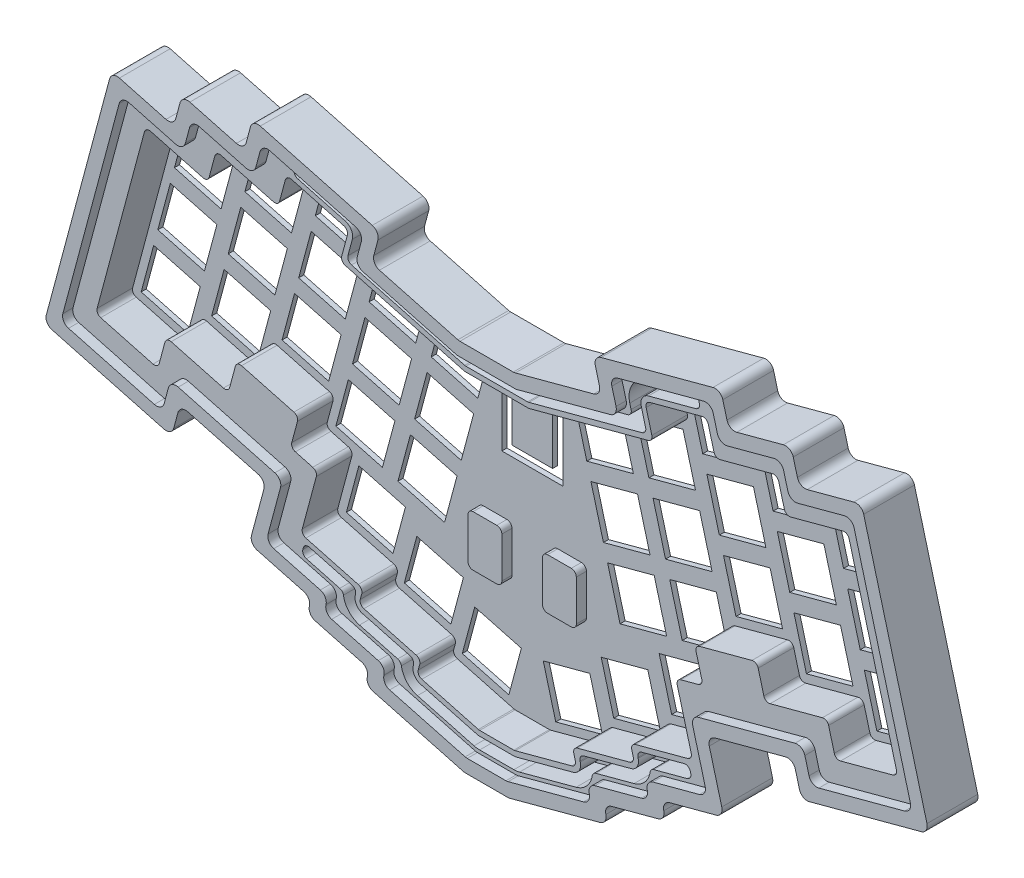
SolidWorks part; units mm, degrees
ref_plane "Front Plane" through (0, 0, 0) normal (0, 0, 1) x (1, 0, 0)
ref_plane "Top Plane" through (0, 0, 0) normal (0, 1, 0) x (1, 0, 0)
ref_plane "Right Plane" through (0, 0, 0) normal (1, 0, 0) x (0, 0, -1)
sketch "Sketch9" plane through (0, 0, 0) normal (0, 0, 1) x (1, 0, 0)
  line L0 (0, 0) -> (-111.0507, 0) construction
  line L1 (0, 0) -> (-97.1816, 26.0397) construction
  line L2 (-9.5, 0) -> (-119.6155, 29.5054)
  line L3 (0, 43.9948) -> (0, -27.2131) construction
  line L4 (-9.5, 0) -> (9.5, 0)
  line L8 (-119.6155, 29.5054) -> (-134.3682, -25.5524)
  line L13 (-117.9362, 26.5966) -> (-121.6243, 12.8322)
  line L14 (-117.9362, 26.5966) -> (-104.1717, 22.9084)
  line L15 (-104.1717, 22.9084) -> (-107.8599, 9.144)
  line L16 (-107.8599, 9.144) -> (-121.6243, 12.8322)
  line L17 (-99.5836, 21.679) -> (-85.8191, 17.9909)
  line L18 (-85.8191, 17.9909) -> (-89.5073, 4.2264)
  line L19 (-89.5073, 4.2264) -> (-103.2717, 7.9146)
  line L20 (-99.5836, 21.679) -> (-103.2717, 7.9146)
  line L21 (-81.231, 16.7615) -> (-67.4665, 13.0733)
  line L22 (-67.4665, 13.0733) -> (-71.1547, -0.6911)
  line L23 (-71.1547, -0.6911) -> (-84.9192, 2.997)
  line L24 (-81.231, 16.7615) -> (-84.9192, 2.997)
  line L25 (-62.8784, 11.8439) -> (-49.114, 8.1557)
  line L26 (-49.114, 8.1557) -> (-52.8021, -5.6087)
  line L27 (-52.8021, -5.6087) -> (-66.5666, -1.9205)
  line L28 (-62.8784, 11.8439) -> (-66.5666, -1.9205)
  line L29 (-44.5258, 6.9264) -> (-30.7614, 3.2382)
  line L30 (-30.7614, 3.2382) -> (-34.4495, -10.5263)
  line L31 (-34.4495, -10.5263) -> (-48.214, -6.8381)
  line L32 (-44.5258, 6.9264) -> (-48.214, -6.8381)
  line L33 (-26.1732, 2.0088) -> (-12.4088, -1.6794)
  line L34 (-12.4088, -1.6794) -> (-16.0969, -15.4438)
  line L35 (-16.0969, -15.4438) -> (-29.8614, -11.7557)
  line L36 (-26.1732, 2.0088) -> (-29.8614, -11.7557)
  line L37 (-104.5011, 3.3264) -> (-90.7367, -0.3617)
  line L38 (-90.7367, -0.3617) -> (-94.4249, -14.1262)
  line L39 (-94.4249, -14.1262) -> (-108.1893, -10.438)
  line L40 (-104.5011, 3.3264) -> (-108.1893, -10.438)
  line L41 (-86.1485, -1.5911) -> (-72.3841, -5.2793)
  line L42 (-72.3841, -5.2793) -> (-76.0723, -19.0437)
  line L43 (-76.0723, -19.0437) -> (-89.8367, -15.3556)
  line L44 (-86.1485, -1.5911) -> (-89.8367, -15.3556)
  line L45 (-67.796, -6.5087) -> (-54.0315, -10.1968)
  line L46 (-54.0315, -10.1968) -> (-57.7197, -23.9613)
  line L47 (-57.7197, -23.9613) -> (-71.4841, -20.2731)
  line L48 (-67.796, -6.5087) -> (-71.4841, -20.2731)
  line L49 (-49.4434, -11.4262) -> (-35.6789, -15.1144)
  line L50 (-35.6789, -15.1144) -> (-39.3671, -28.8789)
  line L51 (-39.3671, -28.8789) -> (-53.1315, -25.1907)
  line L52 (-49.4434, -11.4262) -> (-53.1315, -25.1907)
  line L53 (-31.0908, -16.3438) -> (-17.3263, -20.032)
  line L54 (-17.3263, -20.032) -> (-21.0145, -33.7964)
  line L55 (-21.0145, -33.7964) -> (-34.7789, -30.1082)
  line L56 (-31.0908, -16.3438) -> (-34.7789, -30.1082)
  line L57 (-109.4187, -15.0261) -> (-95.6543, -18.7143)
  line L58 (-95.6543, -18.7143) -> (-99.3424, -32.4788)
  line L59 (-99.3424, -32.4788) -> (-113.1069, -28.7906)
  line L60 (-109.4187, -15.0261) -> (-113.1069, -28.7906)
  line L61 (-91.0661, -19.9437) -> (-77.3017, -23.6319)
  line L62 (-77.3017, -23.6319) -> (-80.9898, -37.3963)
  line L63 (-80.9898, -37.3963) -> (-94.7543, -33.7081)
  line L64 (-91.0661, -19.9437) -> (-94.7543, -33.7081)
  line L65 (-72.7135, -24.8613) -> (-58.9491, -28.5494)
  line L66 (-58.9491, -28.5494) -> (-62.6372, -42.3139)
  line L67 (-62.6372, -42.3139) -> (-76.4017, -38.6257)
  line L68 (-72.7135, -24.8613) -> (-76.4017, -38.6257)
  line L69 (-54.3609, -29.7788) -> (-40.5965, -33.467)
  line L70 (-40.5965, -33.467) -> (-44.2847, -47.2314)
  line L71 (-44.2847, -47.2314) -> (-58.0491, -43.5433)
  line L72 (-54.3609, -29.7788) -> (-58.0491, -43.5433)
  line L73 (-36.0083, -34.6964) -> (-22.2439, -38.3846)
  line L74 (-22.2439, -38.3846) -> (-25.9321, -52.149)
  line L75 (-25.9321, -52.149) -> (-39.6965, -48.4608)
  line L76 (-36.0083, -34.6964) -> (-39.6965, -48.4608)
  line L77 (-122.8537, 8.244) -> (-109.0893, 4.5558)
  line L78 (-109.0893, 4.5558) -> (-112.7775, -9.2086)
  line L79 (-112.7775, -9.2086) -> (-126.5419, -5.5204)
  line L80 (-122.8537, 8.244) -> (-126.5419, -5.5204)
  line L81 (-127.7713, -10.1086) -> (-114.0068, -13.7968)
  line L82 (-114.0068, -13.7968) -> (-117.695, -27.5612)
  line L83 (-117.695, -27.5612) -> (-131.4595, -23.873)
  line L84 (-127.7713, -10.1086) -> (-131.4595, -23.873)
  line L85 (-117.9362, 26.5966) -> (-99.5836, 21.679) construction
  line L86 (-117.9362, 26.5966) -> (-122.8537, 8.244) construction
  line L87 (-51.2492, -50.2829) -> (-37.4848, -53.971)
  line L88 (-51.2492, -50.2829) -> (-54.9374, -64.0473)
  line L89 (-54.9374, -64.0473) -> (-41.173, -67.7355)
  line L90 (-41.173, -67.7355) -> (-37.4848, -53.971)
  line L95 (-134.3682, -25.5524) -> (-52.9286, -47.3741)
  line L96 (-52.9286, -47.3741) -> (-57.8462, -65.7267)
  line L99 (117.9362, 26.5966) -> (122.8537, 8.244) construction
  line L100 (117.9362, 26.5966) -> (99.5836, 21.679) construction
  line L196 (-17.0028, -69.2943) -> (-20.691, -83.0587)
  line L197 (-20.691, -83.0587) -> (-6.9266, -86.7469)
  line L198 (-6.9266, -86.7469) -> (-3.2384, -72.9824)
  line L199 (-3.2384, -72.9824) -> (-17.0028, -69.2943)
  line L295 (-34.126, -59.7886) -> (-37.8142, -73.553)
  line L296 (-37.8142, -73.553) -> (-24.0498, -77.2412)
  line L297 (-34.126, -59.7886) -> (-20.3616, -63.4767)
  line L298 (-20.3616, -63.4767) -> (-24.0498, -77.2412)
  line L299 (-57.8462, -65.7267) -> (-39.4936, -70.6442)
  line L300 (-39.4936, -70.6442) -> (-40.723, -75.2324)
  line L303 (-40.723, -75.2324) -> (-22.3704, -80.1499)
  line L304 (-22.3704, -80.1499) -> (-23.5998, -84.7381)
  line L305 (-23.5998, -84.7381) -> (-5.2472, -89.6557)
  line L306 (-5.2472, -89.6557) -> (5.2472, -89.6557)
  line L307 (23.5998, -84.7381) -> (5.2472, -89.6557)
  line L308 (22.3704, -80.1499) -> (23.5998, -84.7381)
  line L309 (40.723, -75.2324) -> (22.3704, -80.1499)
  line L310 (39.4936, -70.6442) -> (40.723, -75.2324)
  line L311 (57.8462, -65.7267) -> (39.4936, -70.6442)
  line L312 (20.3616, -63.4767) -> (24.0498, -77.2412)
  line L313 (34.126, -59.7886) -> (20.3616, -63.4767)
  line L314 (37.8142, -73.553) -> (24.0498, -77.2412)
  line L315 (34.126, -59.7886) -> (37.8142, -73.553)
  line L316 (3.2384, -72.9824) -> (17.0028, -69.2943)
  line L317 (6.9266, -86.7469) -> (3.2384, -72.9824)
  line L318 (20.691, -83.0587) -> (6.9266, -86.7469)
  line L319 (17.0028, -69.2943) -> (20.691, -83.0587)
  line L320 (52.9286, -47.3741) -> (57.8462, -65.7267)
  line L321 (134.3682, -25.5524) -> (52.9286, -47.3741)
  line L322 (41.173, -67.7355) -> (37.4848, -53.971)
  line L323 (54.9374, -64.0473) -> (41.173, -67.7355)
  line L324 (51.2492, -50.2829) -> (54.9374, -64.0473)
  line L325 (51.2492, -50.2829) -> (37.4848, -53.971)
  line L326 (127.7713, -10.1086) -> (131.4595, -23.873)
  line L327 (117.695, -27.5612) -> (131.4595, -23.873)
  line L328 (114.0068, -13.7968) -> (117.695, -27.5612)
  line L329 (127.7713, -10.1086) -> (114.0068, -13.7968)
  line L330 (122.8537, 8.244) -> (126.5419, -5.5204)
  line L331 (112.7775, -9.2086) -> (126.5419, -5.5204)
  line L332 (109.0893, 4.5558) -> (112.7775, -9.2086)
  line L333 (122.8537, 8.244) -> (109.0893, 4.5558)
  line L334 (36.0083, -34.6964) -> (39.6965, -48.4608)
  line L335 (25.9321, -52.149) -> (39.6965, -48.4608)
  line L336 (22.2439, -38.3846) -> (25.9321, -52.149)
  line L337 (36.0083, -34.6964) -> (22.2439, -38.3846)
  line L338 (54.3609, -29.7788) -> (58.0491, -43.5433)
  line L339 (44.2847, -47.2314) -> (58.0491, -43.5433)
  line L340 (40.5965, -33.467) -> (44.2847, -47.2314)
  line L341 (54.3609, -29.7788) -> (40.5965, -33.467)
  line L342 (72.7135, -24.8613) -> (76.4017, -38.6257)
  line L343 (62.6372, -42.3139) -> (76.4017, -38.6257)
  line L344 (58.9491, -28.5494) -> (62.6372, -42.3139)
  line L345 (72.7135, -24.8613) -> (58.9491, -28.5494)
  line L346 (91.0661, -19.9437) -> (94.7543, -33.7081)
  line L347 (80.9898, -37.3963) -> (94.7543, -33.7081)
  line L348 (77.3017, -23.6319) -> (80.9898, -37.3963)
  line L349 (91.0661, -19.9437) -> (77.3017, -23.6319)
  line L350 (109.4187, -15.0261) -> (113.1069, -28.7906)
  line L351 (99.3424, -32.4788) -> (113.1069, -28.7906)
  line L352 (95.6543, -18.7143) -> (99.3424, -32.4788)
  line L353 (109.4187, -15.0261) -> (95.6543, -18.7143)
  line L354 (31.0908, -16.3438) -> (34.7789, -30.1082)
  line L355 (21.0145, -33.7964) -> (34.7789, -30.1082)
  line L356 (17.3263, -20.032) -> (21.0145, -33.7964)
  line L357 (31.0908, -16.3438) -> (17.3263, -20.032)
  line L358 (49.4434, -11.4262) -> (53.1315, -25.1907)
  line L359 (39.3671, -28.8789) -> (53.1315, -25.1907)
  line L360 (35.6789, -15.1144) -> (39.3671, -28.8789)
  line L361 (49.4434, -11.4262) -> (35.6789, -15.1144)
  line L362 (67.796, -6.5087) -> (71.4841, -20.2731)
  line L363 (57.7197, -23.9613) -> (71.4841, -20.2731)
  line L364 (54.0315, -10.1968) -> (57.7197, -23.9613)
  line L365 (67.796, -6.5087) -> (54.0315, -10.1968)
  line L366 (86.1485, -1.5911) -> (89.8367, -15.3556)
  line L367 (76.0723, -19.0437) -> (89.8367, -15.3556)
  line L368 (72.3841, -5.2793) -> (76.0723, -19.0437)
  line L369 (86.1485, -1.5911) -> (72.3841, -5.2793)
  line L370 (104.5011, 3.3264) -> (108.1893, -10.438)
  line L371 (94.4249, -14.1262) -> (108.1893, -10.438)
  line L372 (90.7367, -0.3617) -> (94.4249, -14.1262)
  line L373 (104.5011, 3.3264) -> (90.7367, -0.3617)
  line L374 (26.1732, 2.0088) -> (29.8614, -11.7557)
  line L375 (16.0969, -15.4438) -> (29.8614, -11.7557)
  line L376 (12.4088, -1.6794) -> (16.0969, -15.4438)
  line L377 (26.1732, 2.0088) -> (12.4088, -1.6794)
  line L378 (44.5258, 6.9264) -> (48.214, -6.8381)
  line L379 (34.4495, -10.5263) -> (48.214, -6.8381)
  line L380 (30.7614, 3.2382) -> (34.4495, -10.5263)
  line L381 (44.5258, 6.9264) -> (30.7614, 3.2382)
  line L382 (62.8784, 11.8439) -> (66.5666, -1.9205)
  line L383 (52.8021, -5.6087) -> (66.5666, -1.9205)
  line L384 (49.114, 8.1557) -> (52.8021, -5.6087)
  line L385 (62.8784, 11.8439) -> (49.114, 8.1557)
  line L386 (81.231, 16.7615) -> (84.9192, 2.997)
  line L387 (71.1547, -0.6911) -> (84.9192, 2.997)
  line L388 (67.4665, 13.0733) -> (71.1547, -0.6911)
  line L389 (81.231, 16.7615) -> (67.4665, 13.0733)
  line L390 (99.5836, 21.679) -> (103.2717, 7.9146)
  line L391 (89.5073, 4.2264) -> (103.2717, 7.9146)
  line L392 (85.8191, 17.9909) -> (89.5073, 4.2264)
  line L393 (99.5836, 21.679) -> (85.8191, 17.9909)
  line L394 (107.8599, 9.144) -> (121.6243, 12.8322)
  line L395 (104.1717, 22.9084) -> (107.8599, 9.144)
  line L396 (117.9362, 26.5966) -> (104.1717, 22.9084)
  line L397 (117.9362, 26.5966) -> (121.6243, 12.8322)
  line L398 (119.6155, 29.5054) -> (134.3682, -25.5524)
  line L399 (9.5, 0) -> (119.6155, 29.5054)
  point P4 (0, -89.6557)
  point P101 (0, -84.1455)
  point P102 (0, -74.6398)
  dimension "D1" = 15
  dimension "D2" = 19
  dimension "D3" = 14.25
  dimension "D4" = 14.25
  dimension "D5" = 0
  dimension "D6" = 114
  dimension "D7" = 90
  dimension "D8" = 57
  dimension "D9" = 2.375
  dimension "D10" = 2.375
  dimension "D11" = 14.25
  dimension "D12" = 14.25
  dimension "D15" = 90
  dimension "D16" = 14.25
  dimension "D17" = 14.25
  dimension "D18" = 4.75
  dimension "D19" = 8.3125
  dimension "D21" = 14.25
  dimension "D22" = 2.375
  dimension "D23" = 14.25
  dimension "D24" = 2.375
  dimension "D20" = 4.75
  dimension "D25" = 4.75
  dimension "D26" = 4.75
  dimension "D27" = 4.75
  dimension "D28" = 4.75
  dimension "D29" = 4.75
  dimension "D13" = 6
  dimension "D14" = 3
extrude "Boss-Extrude1" add sketch "Sketch9" along normal blind 1.5
sketch "Sketch13" plane through (0, 0, 1.5) normal (0, 0, 1) x (1, 0, 0)
  line L0 (-119.6155, 29.5054) -> (-101.263, 24.5878)
  line L1 (-9.5, 0) -> (-119.6155, 29.5054) construction
  line L2 (-101.263, 24.5878) -> (-116.0156, -30.47)
  line L3 (-134.3682, -25.5524) -> (-52.9286, -47.3741) construction
  line L4 (-116.0156, -30.47) -> (-134.3682, -25.5524)
  line L5 (-134.3682, -25.5524) -> (-119.6155, 29.5054)
  line L6 (-107.8599, 9.144) -> (-104.1717, 22.9084) construction
  line L7 (0, 0) -> (0, 22.9807) construction
  line L8 (134.3682, -25.5524) -> (119.6155, 29.5054)
  line L9 (116.0156, -30.47) -> (134.3682, -25.5524)
  line L10 (101.263, 24.5878) -> (116.0156, -30.47)
  line L11 (119.6155, 29.5054) -> (101.263, 24.5878)
  dimension "D1" = 2.375
extrude "Cut-Extrude4" cut sketch "Sketch13" against normal through all
sketch "Sketch10" plane through (0, 0, 1.5) normal (0, 0, 1) x (1, 0, 0)
  line L0 (-9, -25.375) -> (9, -25.375)
  line L1 (9.5, 0) -> (-9.5, 0) construction
  line L2 (-9, -25.375) -> (-9, -2.375)
  line L3 (-9, -2.375) -> (-6, -2.375)
  line L4 (-6, -2.375) -> (-6, -22.375)
  line L5 (-6, -22.375) -> (6, -22.375)
  line L6 (6, -22.375) -> (6, -2.375)
  line L7 (6, -2.375) -> (9, -2.375)
  line L8 (9, -2.375) -> (9, -25.375)
  dimension "D1" = 18
  dimension "D2" = 9
  dimension "D3" = 25.375
  dimension "D4" = 23
  dimension "D5" = 3
  dimension "D6" = 3
  dimension "D7" = 3
extrude "Cut-Extrude1" cut sketch "Sketch10" against normal through all
sketch "Sketch16" plane through (0, 0, 1.5) normal (0, 0, 1) x (1, 0, 0)
  line L0 (-64.5578, 14.7527) -> (-46.2052, 9.8351)
  line L1 (-9.5, 0) -> (-101.263, 24.5878) construction
  line L2 (-46.2052, 9.8351) -> (-60.9579, -45.2226)
  line L3 (-116.0156, -30.47) -> (-52.9286, -47.3741) construction
  line L4 (-60.9579, -45.2226) -> (-79.3105, -40.3051)
  line L5 (-79.3105, -40.3051) -> (-64.5578, 14.7527)
  line L6 (-62.8784, 11.8439) -> (-66.5666, -1.9205) construction
  line L7 (-52.8021, -5.6087) -> (-49.114, 8.1557) construction
  line L8 (-62.8784, 11.8439) -> (-49.114, 8.1557)
  line L9 (-49.114, 8.1557) -> (-52.8021, -5.6087)
  line L10 (-52.8021, -5.6087) -> (-66.5666, -1.9205)
  line L11 (-66.5666, -1.9205) -> (-62.8784, 11.8439)
  line L12 (-54.0315, -10.1968) -> (-57.7197, -23.9613)
  line L13 (-57.7197, -23.9613) -> (-71.4841, -20.2731)
  line L14 (-71.4841, -20.2731) -> (-67.796, -6.5087)
  line L15 (-67.796, -6.5087) -> (-54.0315, -10.1968)
  line L16 (-58.9491, -28.5494) -> (-62.6372, -42.3139)
  line L17 (-62.6372, -42.3139) -> (-76.4017, -38.6257)
  line L18 (-76.4017, -38.6257) -> (-72.7135, -24.8613)
  line L19 (-72.7135, -24.8613) -> (-58.9491, -28.5494)
  line L20 (-101.263, 24.5878) -> (-82.9104, 19.6702)
  line L21 (-82.9104, 19.6702) -> (-97.663, -35.3875)
  line L22 (-97.663, -35.3875) -> (-116.0156, -30.47)
  line L23 (-116.0156, -30.47) -> (-101.263, 24.5878)
  line L24 (-89.5073, 4.2264) -> (-85.8191, 17.9909) construction
  line L25 (0, 0) -> (0, -96.8521) construction
  line L26 (116.0156, -30.47) -> (101.263, 24.5878)
  line L27 (97.663, -35.3875) -> (116.0156, -30.47)
  line L28 (82.9104, 19.6702) -> (97.663, -35.3875)
  line L29 (101.263, 24.5878) -> (82.9104, 19.6702)
  line L30 (72.7135, -24.8613) -> (58.9491, -28.5494)
  line L31 (76.4017, -38.6257) -> (72.7135, -24.8613)
  line L32 (62.6372, -42.3139) -> (76.4017, -38.6257)
  line L33 (58.9491, -28.5494) -> (62.6372, -42.3139)
  line L34 (67.796, -6.5087) -> (54.0315, -10.1968)
  line L35 (71.4841, -20.2731) -> (67.796, -6.5087)
  line L36 (57.7197, -23.9613) -> (71.4841, -20.2731)
  line L37 (54.0315, -10.1968) -> (57.7197, -23.9613)
  line L38 (66.5666, -1.9205) -> (62.8784, 11.8439)
  line L39 (52.8021, -5.6087) -> (66.5666, -1.9205)
  line L40 (49.114, 8.1557) -> (52.8021, -5.6087)
  line L41 (62.8784, 11.8439) -> (49.114, 8.1557)
  line L42 (79.3105, -40.3051) -> (64.5578, 14.7527)
  line L43 (60.9579, -45.2226) -> (79.3105, -40.3051)
  line L44 (46.2052, 9.8351) -> (60.9579, -45.2226)
  line L45 (64.5578, 14.7527) -> (46.2052, 9.8351)
  dimension "D1" = 2.375
  dimension "D2" = 2.375
  dimension "D3" = 2.375
extrude "Cut-Extrude6" cut sketch "Sketch16" against normal through all
sketch "Sketch17" plane through (0, 0, 0) normal (0, 0, 1) x (1, 0, 0)
  line L22 (-64.5578, 14.7527) -> (-76.8517, -31.1288)
  line L23 (-58.4991, -36.0464) -> (-46.2052, 9.8351)
  line L24 (-64.5578, 14.7527) -> (-62.099, 23.929)
  line L25 (-62.099, 23.929) -> (-43.7464, 19.0114)
  line L26 (-43.7464, 19.0114) -> (-46.2052, 9.8351)
  line L27 (-76.8517, -31.1288) -> (-58.4991, -36.0464)
  line L28 (-97.663, -35.3875) -> (-79.3105, -40.3051) construction
  line L29 (-60.4196, 21.0202) -> (-46.6552, 17.332)
  line L30 (-46.6552, 17.332) -> (-50.3433, 3.5676)
  line L31 (-50.3433, 3.5676) -> (-64.1078, 7.2558)
  line L32 (-64.1078, 7.2558) -> (-60.4196, 21.0202)
  line L33 (-65.3372, 2.6676) -> (-51.5727, -1.0206)
  line L34 (-51.5727, -1.0206) -> (-55.2609, -14.785)
  line L35 (-69.0253, -11.0968) -> (-65.3372, 2.6676)
  line L36 (-55.2609, -14.785) -> (-69.0253, -11.0968)
  line L37 (-70.2547, -15.685) -> (-56.4903, -19.3731)
  line L38 (-56.4903, -19.3731) -> (-60.1785, -33.1376)
  line L39 (-73.9429, -29.4494) -> (-70.2547, -15.685)
  line L40 (-60.1785, -33.1376) -> (-73.9429, -29.4494)
  line L41 (-85.3691, 10.494) -> (-103.7217, 15.4115)
  line L42 (-97.663, -35.3875) -> (-82.9104, 19.6702) construction
  line L43 (-103.7217, 15.4115) -> (-118.4744, -39.6463)
  line L44 (-118.4744, -39.6463) -> (-100.1218, -44.5638)
  line L45 (-100.1218, -44.5638) -> (-97.663, -35.3875)
  line L46 (-97.663, -35.3875) -> (-79.3105, -40.3051) construction
  line L47 (-64.5578, 14.7527) -> (-82.9104, 19.6702) construction
  line L48 (-85.3691, 10.494) -> (-97.663, -35.3875)
  line L49 (-102.0424, 12.5027) -> (-88.2779, 8.8146)
  line L50 (-88.2779, 8.8146) -> (-91.9661, -4.9499)
  line L51 (-91.9661, -4.9499) -> (-105.7305, -1.2617)
  line L52 (-105.7305, -1.2617) -> (-102.0424, 12.5027)
  line L53 (-106.9599, -5.8498) -> (-93.1955, -9.538)
  line L54 (-110.6481, -19.6143) -> (-106.9599, -5.8498)
  line L55 (-93.1955, -9.538) -> (-96.8836, -23.3025)
  line L56 (-96.8836, -23.3025) -> (-110.6481, -19.6143)
  line L57 (-111.8775, -24.2024) -> (-98.113, -27.8906)
  line L58 (-115.5657, -37.9669) -> (-111.8775, -24.2024)
  line L59 (-98.113, -27.8906) -> (-101.8012, -41.6551)
  line L60 (-101.8012, -41.6551) -> (-115.5657, -37.9669)
  line L61 (0, 16.4321) -> (0, -96.6777) construction
  line L62 (101.8012, -41.6551) -> (115.5657, -37.9669)
  line L63 (98.113, -27.8906) -> (101.8012, -41.6551)
  line L64 (115.5657, -37.9669) -> (111.8775, -24.2024)
  line L65 (111.8775, -24.2024) -> (98.113, -27.8906)
  line L66 (96.8836, -23.3025) -> (110.6481, -19.6143)
  line L67 (93.1955, -9.538) -> (96.8836, -23.3025)
  line L68 (110.6481, -19.6143) -> (106.9599, -5.8498)
  line L69 (106.9599, -5.8498) -> (93.1955, -9.538)
  line L70 (105.7305, -1.2617) -> (102.0424, 12.5027)
  line L71 (91.9661, -4.9499) -> (105.7305, -1.2617)
  line L72 (88.2779, 8.8146) -> (91.9661, -4.9499)
  line L73 (102.0424, 12.5027) -> (88.2779, 8.8146)
  line L74 (85.3691, 10.494) -> (97.663, -35.3875)
  line L75 (100.1218, -44.5638) -> (97.663, -35.3875)
  line L76 (118.4744, -39.6463) -> (100.1218, -44.5638)
  line L77 (103.7217, 15.4115) -> (118.4744, -39.6463)
  line L78 (85.3691, 10.494) -> (103.7217, 15.4115)
  line L79 (60.1785, -33.1376) -> (73.9429, -29.4494)
  line L80 (73.9429, -29.4494) -> (70.2547, -15.685)
  line L81 (56.4903, -19.3731) -> (60.1785, -33.1376)
  line L82 (70.2547, -15.685) -> (56.4903, -19.3731)
  line L83 (55.2609, -14.785) -> (69.0253, -11.0968)
  line L84 (69.0253, -11.0968) -> (65.3372, 2.6676)
  line L85 (51.5727, -1.0206) -> (55.2609, -14.785)
  line L86 (65.3372, 2.6676) -> (51.5727, -1.0206)
  line L87 (64.1078, 7.2558) -> (60.4196, 21.0202)
  line L88 (50.3433, 3.5676) -> (64.1078, 7.2558)
  line L89 (46.6552, 17.332) -> (50.3433, 3.5676)
  line L90 (60.4196, 21.0202) -> (46.6552, 17.332)
  line L91 (76.8517, -31.1288) -> (58.4991, -36.0464)
  line L92 (43.7464, 19.0114) -> (46.2052, 9.8351)
  line L93 (62.099, 23.929) -> (43.7464, 19.0114)
  line L94 (64.5578, 14.7527) -> (62.099, 23.929)
  line L95 (58.4991, -36.0464) -> (46.2052, 9.8351)
  line L96 (64.5578, 14.7527) -> (76.8517, -31.1288)
  point P12 (-52.9227, 21.4702)
  dimension "D1" = 9.5
  dimension "D2" = 9.5
  dimension "D3" = 14.25
  dimension "D4" = 2.375
  dimension "D5" = 2.375
  dimension "D6" = 2.375
  dimension "D8" = 19
  dimension "D9" = 9.5
  dimension "D10" = 9.5
  dimension "D11" = 14.25
  dimension "D12" = 14.25
  dimension "D13" = 2.375
  dimension "D14" = 2.375
  dimension "D7" = 3
  dimension "D15" = 3
extrude "Boss-Extrude3" add sketch "Sketch17" along normal blind 1.5
sketch "Sketch14" plane through (0, 0, 1.5) normal (0, 0, 1) x (1, 0, 0)
  line L53 (-9.5, 0) -> (-46.2052, 9.8351)
  line L54 (-46.2052, 9.8351) -> (-43.7464, 19.0114)
  line L55 (-60.9579, -45.2226) -> (-52.9286, -47.3741)
  line L56 (-52.9286, -47.3741) -> (-57.8462, -65.7267)
  line L57 (-46.2052, 9.8351) -> (-43.7464, 19.0114)
  line L58 (-43.7464, 19.0114) -> (-62.099, 23.929)
  line L61 (5.2472, -89.6557) -> (23.5998, -84.7381)
  line L63 (5.2472, -89.6557) -> (23.5998, -84.7381)
  line L65 (23.5998, -84.7381) -> (22.3704, -80.1499)
  line L66 (9.5, 0) -> (-9.5, 0)
  line L67 (-9.5, 0) -> (-46.2052, 9.8351)
  line L69 (-60.9579, -45.2226) -> (-52.9286, -47.3741)
  line L70 (-52.9286, -47.3741) -> (-57.8462, -65.7267)
  line L80 (9.5, 0) -> (-9.5, 0)
  line L92 (6.5637, -99.6557) -> (35.8472, -91.8092)
  line L95 (-8.1835, 10) -> (-33.9577, 16.9062)
  line L98 (-65.1761, -54.4451) -> (-70.0936, -72.7977)
  line L99 (-33.9577, 16.9062) -> (-31.499, 26.0825)
  line L103 (-33.9577, 16.9062) -> (-31.499, 26.0825)
  line L150 (8.1835, 10) -> (-8.1835, 10)
  line L151 (-8.1835, 10) -> (-33.9577, 16.9062)
  line L154 (-65.1761, -54.4451) -> (-70.0936, -72.7977)
  line L164 (8.1835, 10) -> (-8.1835, 10)
  line L171 (23.5998, -84.7381) -> (22.3704, -80.1499)
  line L174 (22.3704, -80.1499) -> (40.723, -75.2324)
  line L176 (22.3704, -80.1499) -> (40.723, -75.2324)
  line L178 (40.723, -75.2324) -> (39.4936, -70.6442)
  line L193 (-43.7464, 19.0114) -> (-62.099, 23.929)
  line L194 (-62.099, 23.929) -> (-64.5578, 14.7527)
  line L195 (-62.099, 23.929) -> (-64.5578, 14.7527)
  line L196 (-64.5578, 14.7527) -> (-82.9104, 19.6702)
  line L197 (-64.5578, 14.7527) -> (-82.9104, 19.6702)
  line L198 (-82.9104, 19.6702) -> (-85.3691, 10.494)
  line L199 (-82.9104, 19.6702) -> (-85.3691, 10.494)
  line L200 (-85.3691, 10.494) -> (-103.7217, 15.4115)
  line L201 (-85.3691, 10.494) -> (-103.7217, 15.4115)
  line L202 (-103.7217, 15.4115) -> (-118.4744, -39.6463)
  line L203 (-103.7217, 15.4115) -> (-118.4744, -39.6463)
  line L204 (-118.4744, -39.6463) -> (-100.1218, -44.5638)
  line L205 (-118.4744, -39.6463) -> (-100.1218, -44.5638)
  line L206 (-100.1218, -44.5638) -> (-97.663, -35.3875)
  line L207 (-100.1218, -44.5638) -> (-97.663, -35.3875)
  line L208 (-97.663, -35.3875) -> (-79.3105, -40.3051)
  line L209 (-97.663, -35.3875) -> (-79.3105, -40.3051)
  line L210 (-79.3105, -40.3051) -> (-76.8517, -31.1288)
  line L211 (-79.3105, -40.3051) -> (-76.8517, -31.1288)
  line L212 (-76.8517, -31.1288) -> (-58.4991, -36.0464)
  line L213 (-76.8517, -31.1288) -> (-58.4991, -36.0464)
  line L214 (-58.4991, -36.0464) -> (-60.9579, -45.2226)
  line L215 (-58.4991, -36.0464) -> (-60.9579, -45.2226)
  line L216 (-57.8462, -65.7267) -> (-39.4936, -70.6442)
  line L217 (-57.8462, -65.7267) -> (-39.4936, -70.6442)
  line L218 (-39.4936, -70.6442) -> (-40.723, -75.2324)
  line L219 (-39.4936, -70.6442) -> (-40.723, -75.2324)
  line L220 (-40.723, -75.2324) -> (-22.3704, -80.1499)
  line L221 (-40.723, -75.2324) -> (-22.3704, -80.1499)
  line L222 (-22.3704, -80.1499) -> (-23.5998, -84.7381)
  line L223 (-22.3704, -80.1499) -> (-23.5998, -84.7381)
  line L224 (-23.5998, -84.7381) -> (-5.2472, -89.6557)
  line L225 (-23.5998, -84.7381) -> (-5.2472, -89.6557)
  line L226 (-5.2472, -89.6557) -> (5.2472, -89.6557)
  line L227 (-5.2472, -89.6557) -> (5.2472, -89.6557)
  line L228 (-31.499, 26.0825) -> (-69.1701, 36.1764)
  line L229 (-31.499, 26.0825) -> (-69.1701, 36.1764)
  line L230 (-69.1701, 36.1764) -> (-71.6288, 27.0001)
  line L231 (-69.1701, 36.1764) -> (-71.6288, 27.0001)
  line L232 (-71.6288, 27.0001) -> (-89.9814, 31.9177)
  line L233 (-71.6288, 27.0001) -> (-89.9814, 31.9177)
  line L234 (-89.9814, 31.9177) -> (-92.4402, 22.7414)
  line L235 (-89.9814, 31.9177) -> (-92.4402, 22.7414)
  line L236 (-92.4402, 22.7414) -> (-110.7928, 27.659)
  line L237 (-92.4402, 22.7414) -> (-110.7928, 27.659)
  line L238 (-110.7928, 27.659) -> (-130.7219, -46.7173)
  line L239 (-110.7928, 27.659) -> (-130.7219, -46.7173)
  line L240 (-130.7219, -46.7173) -> (-93.0508, -56.8113)
  line L241 (-130.7219, -46.7173) -> (-93.0508, -56.8113)
  line L242 (-93.0508, -56.8113) -> (-90.592, -47.635)
  line L243 (-93.0508, -56.8113) -> (-90.592, -47.635)
  line L244 (-90.592, -47.635) -> (-65.1761, -54.4451)
  line L245 (-90.592, -47.635) -> (-65.1761, -54.4451)
  line L252 (-70.0936, -72.7977) -> (-51.741, -77.7153)
  line L253 (-70.0936, -72.7977) -> (-51.741, -77.7153)
  line L254 (-51.741, -77.7153) -> (-52.9704, -82.3034)
  line L255 (-51.741, -77.7153) -> (-52.9704, -82.3034)
  line L256 (-52.9704, -82.3034) -> (-34.6178, -87.221)
  line L257 (-52.9704, -82.3034) -> (-34.6178, -87.221)
  line L258 (-34.6178, -87.221) -> (-35.8472, -91.8092)
  line L259 (-34.6178, -87.221) -> (-35.8472, -91.8092)
  line L260 (-35.8472, -91.8092) -> (-6.5637, -99.6557)
  line L261 (-35.8472, -91.8092) -> (-6.5637, -99.6557)
  line L262 (-6.5637, -99.6557) -> (6.5637, -99.6557)
  line L263 (-6.5637, -99.6557) -> (6.5637, -99.6557)
  line L278 (40.723, -75.2324) -> (39.4936, -70.6442)
  line L279 (39.4936, -70.6442) -> (57.8462, -65.7267)
  line L280 (39.4936, -70.6442) -> (57.8462, -65.7267)
  line L281 (57.8462, -65.7267) -> (52.9286, -47.3741)
  line L282 (57.8462, -65.7267) -> (52.9286, -47.3741)
  line L283 (52.9286, -47.3741) -> (60.9579, -45.2226)
  line L284 (52.9286, -47.3741) -> (60.9579, -45.2226)
  line L285 (60.9579, -45.2226) -> (58.4991, -36.0464)
  line L286 (60.9579, -45.2226) -> (58.4991, -36.0464)
  line L287 (58.4991, -36.0464) -> (76.8517, -31.1288)
  line L288 (58.4991, -36.0464) -> (76.8517, -31.1288)
  line L289 (76.8517, -31.1288) -> (79.3105, -40.3051)
  line L290 (76.8517, -31.1288) -> (79.3105, -40.3051)
  line L291 (79.3105, -40.3051) -> (97.663, -35.3875)
  line L292 (79.3105, -40.3051) -> (97.663, -35.3875)
  line L293 (97.663, -35.3875) -> (100.1218, -44.5638)
  line L294 (97.663, -35.3875) -> (100.1218, -44.5638)
  line L295 (100.1218, -44.5638) -> (118.4744, -39.6463)
  line L296 (100.1218, -44.5638) -> (118.4744, -39.6463)
  line L297 (118.4744, -39.6463) -> (103.7217, 15.4115)
  line L298 (118.4744, -39.6463) -> (103.7217, 15.4115)
  line L299 (103.7217, 15.4115) -> (85.3691, 10.494)
  line L300 (103.7217, 15.4115) -> (85.3691, 10.494)
  line L301 (85.3691, 10.494) -> (82.9104, 19.6702)
  line L302 (85.3691, 10.494) -> (82.9104, 19.6702)
  line L303 (82.9104, 19.6702) -> (64.5578, 14.7527)
  line L304 (82.9104, 19.6702) -> (64.5578, 14.7527)
  line L305 (64.5578, 14.7527) -> (62.099, 23.929)
  line L306 (64.5578, 14.7527) -> (62.099, 23.929)
  line L307 (62.099, 23.929) -> (43.7464, 19.0114)
  line L308 (62.099, 23.929) -> (43.7464, 19.0114)
  line L309 (43.7464, 19.0114) -> (46.2052, 9.8351)
  line L310 (43.7464, 19.0114) -> (46.2052, 9.8351)
  line L311 (46.2052, 9.8351) -> (9.5, 0)
  line L312 (46.2052, 9.8351) -> (9.5, 0)
  line L313 (6.5637, -99.6557) -> (35.8472, -91.8092)
  line L314 (35.8472, -91.8092) -> (34.6178, -87.221)
  line L315 (35.8472, -91.8092) -> (34.6178, -87.221)
  line L316 (34.6178, -87.221) -> (52.9704, -82.3034)
  line L317 (34.6178, -87.221) -> (52.9704, -82.3034)
  line L318 (52.9704, -82.3034) -> (51.741, -77.7153)
  line L319 (52.9704, -82.3034) -> (51.741, -77.7153)
  line L320 (51.741, -77.7153) -> (70.0936, -72.7977)
  line L321 (51.741, -77.7153) -> (70.0936, -72.7977)
  line L322 (70.0936, -72.7977) -> (65.1761, -54.4451)
  line L323 (70.0936, -72.7977) -> (65.1761, -54.4451)
  line L324 (65.1761, -54.4451) -> (90.592, -47.635)
  line L325 (65.1761, -54.4451) -> (90.592, -47.635)
  line L334 (90.592, -47.635) -> (93.0508, -56.8113)
  line L335 (90.592, -47.635) -> (93.0508, -56.8113)
  line L336 (93.0508, -56.8113) -> (130.7219, -46.7173)
  line L337 (93.0508, -56.8113) -> (130.7219, -46.7173)
  line L338 (130.7219, -46.7173) -> (110.7928, 27.659)
  line L339 (130.7219, -46.7173) -> (110.7928, 27.659)
  line L340 (110.7928, 27.659) -> (92.4402, 22.7414)
  line L341 (110.7928, 27.659) -> (92.4402, 22.7414)
  line L342 (92.4402, 22.7414) -> (89.9814, 31.9177)
  line L343 (92.4402, 22.7414) -> (89.9814, 31.9177)
  line L344 (89.9814, 31.9177) -> (71.6288, 27.0001)
  line L345 (89.9814, 31.9177) -> (71.6288, 27.0001)
  line L346 (71.6288, 27.0001) -> (69.1701, 36.1764)
  line L347 (71.6288, 27.0001) -> (69.1701, 36.1764)
  line L348 (69.1701, 36.1764) -> (31.499, 26.0825)
  line L349 (69.1701, 36.1764) -> (31.499, 26.0825)
  line L350 (31.499, 26.0825) -> (33.9577, 16.9062)
  line L351 (31.499, 26.0825) -> (33.9577, 16.9062)
  line L352 (33.9577, 16.9062) -> (8.1835, 10)
  line L353 (33.9577, 16.9062) -> (8.1835, 10)
  dimension "D1" = 0
  dimension "D2" = 10
extrude "Boss-Extrude2" add sketch "Sketch14" along normal blind 13.5 and the other way blind 1.5
sketch "Sketch18" plane through (0, 0, 15) normal (0, 0, 1) x (1, 0, 0)
  line L0 (-79.3105, -40.3051) -> (-76.8517, -31.1288)
  line L1 (-76.8517, -31.1288) -> (-58.4991, -36.0464)
  line L2 (-58.4991, -36.0464) -> (-60.9579, -45.2226)
  line L3 (-60.9579, -45.2226) -> (-52.9286, -47.3741)
  line L4 (60.9579, -45.2226) -> (58.4991, -36.0464)
  line L5 (58.4991, -36.0464) -> (76.8517, -31.1288)
  line L6 (76.8517, -31.1288) -> (79.3105, -40.3051)
  line L7 (79.3105, -40.3051) -> (97.663, -35.3875)
  line L88 (23.5998, -84.7381) -> (22.3704, -80.1499)
  line L89 (22.3704, -80.1499) -> (40.723, -75.2324)
  line L90 (40.723, -75.2324) -> (39.4936, -70.6442)
  line L91 (39.4936, -70.6442) -> (57.8462, -65.7267)
  line L92 (57.8462, -65.7267) -> (52.9286, -47.3741)
  line L93 (52.9286, -47.3741) -> (97.663, -35.3875)
  line L98 (97.663, -35.3875) -> (100.1218, -44.5638)
  line L99 (100.1218, -44.5638) -> (118.4744, -39.6463)
  line L100 (118.4744, -39.6463) -> (103.7217, 15.4115)
  line L101 (103.7217, 15.4115) -> (85.3691, 10.494)
  line L102 (85.3691, 10.494) -> (82.9104, 19.6702)
  line L103 (82.9104, 19.6702) -> (64.5578, 14.7527)
  line L104 (64.5578, 14.7527) -> (62.099, 23.929)
  line L105 (62.099, 23.929) -> (43.7464, 19.0114)
  line L106 (43.7464, 19.0114) -> (46.2052, 9.8351)
  line L107 (46.2052, 9.8351) -> (9.5, 0)
  line L108 (9.5, 0) -> (-9.5, 0)
  line L109 (-9.5, 0) -> (-46.2052, 9.8351)
  line L110 (-46.2052, 9.8351) -> (-43.7464, 19.0114)
  line L111 (-43.7464, 19.0114) -> (-62.099, 23.929)
  line L112 (-62.099, 23.929) -> (-64.5578, 14.7527)
  line L113 (-64.5578, 14.7527) -> (-82.9104, 19.6702)
  line L114 (-82.9104, 19.6702) -> (-85.3691, 10.494)
  line L115 (-85.3691, 10.494) -> (-103.7217, 15.4115)
  line L116 (-103.7217, 15.4115) -> (-118.4744, -39.6463)
  line L117 (-118.4744, -39.6463) -> (-100.1218, -44.5638)
  line L118 (-100.1218, -44.5638) -> (-97.663, -35.3875)
  line L119 (-97.663, -35.3875) -> (-52.9286, -47.3741)
  line L124 (-52.9286, -47.3741) -> (-57.8462, -65.7267)
  line L125 (-57.8462, -65.7267) -> (-39.4936, -70.6442)
  line L126 (-39.4936, -70.6442) -> (-40.723, -75.2324)
  line L127 (-40.723, -75.2324) -> (-22.3704, -80.1499)
  line L128 (-22.3704, -80.1499) -> (-23.5998, -84.7381)
  line L129 (-23.5998, -84.7381) -> (-5.2472, -89.6557)
  line L130 (-5.2472, -89.6557) -> (5.2472, -89.6557)
  line L131 (5.2472, -89.6557) -> (23.5998, -84.7381)
  line L132 (23.5998, -84.7381) -> (22.3704, -80.1499)
  line L133 (22.3704, -80.1499) -> (40.723, -75.2324)
  line L134 (40.723, -75.2324) -> (39.4936, -70.6442)
  line L135 (39.4936, -70.6442) -> (57.8462, -65.7267)
  line L136 (57.8462, -65.7267) -> (52.9286, -47.3741)
  line L137 (52.9286, -47.3741) -> (60.9579, -45.2226)
  line L142 (97.663, -35.3875) -> (100.1218, -44.5638)
  line L143 (100.1218, -44.5638) -> (118.4744, -39.6463)
  line L144 (118.4744, -39.6463) -> (103.7217, 15.4115)
  line L145 (103.7217, 15.4115) -> (85.3691, 10.494)
  line L146 (85.3691, 10.494) -> (82.9104, 19.6702)
  line L147 (82.9104, 19.6702) -> (64.5578, 14.7527)
  line L148 (64.5578, 14.7527) -> (62.099, 23.929)
  line L149 (62.099, 23.929) -> (43.7464, 19.0114)
  line L150 (43.7464, 19.0114) -> (46.2052, 9.8351)
  line L151 (46.2052, 9.8351) -> (9.5, 0)
  line L152 (9.5, 0) -> (-9.5, 0)
  line L153 (-9.5, 0) -> (-46.2052, 9.8351)
  line L154 (-46.2052, 9.8351) -> (-43.7464, 19.0114)
  line L155 (-43.7464, 19.0114) -> (-62.099, 23.929)
  line L156 (-62.099, 23.929) -> (-64.5578, 14.7527)
  line L157 (-64.5578, 14.7527) -> (-82.9104, 19.6702)
  line L158 (-82.9104, 19.6702) -> (-85.3691, 10.494)
  line L159 (-85.3691, 10.494) -> (-103.7217, 15.4115)
  line L160 (-103.7217, 15.4115) -> (-118.4744, -39.6463)
  line L161 (-118.4744, -39.6463) -> (-100.1218, -44.5638)
  line L162 (-100.1218, -44.5638) -> (-97.663, -35.3875)
  line L163 (-97.663, -35.3875) -> (-79.3105, -40.3051)
  line L168 (-52.9286, -47.3741) -> (-57.8462, -65.7267)
  line L169 (-57.8462, -65.7267) -> (-39.4936, -70.6442)
  line L170 (-39.4936, -70.6442) -> (-40.723, -75.2324)
  line L171 (-40.723, -75.2324) -> (-22.3704, -80.1499)
  line L172 (-22.3704, -80.1499) -> (-23.5998, -84.7381)
  line L173 (-23.5998, -84.7381) -> (-5.2472, -89.6557)
  line L174 (-5.2472, -89.6557) -> (5.2472, -89.6557)
  line L175 (5.2472, -89.6557) -> (23.5998, -84.7381)
  line L220 (30.9482, -88.9807) -> (29.7188, -84.3926)
  line L221 (29.7188, -84.3926) -> (48.0714, -79.475)
  line L222 (48.0714, -79.475) -> (46.842, -74.8869)
  line L223 (46.842, -74.8869) -> (65.1946, -69.9693)
  line L224 (65.1946, -69.9693) -> (60.2771, -51.6167)
  line L225 (60.2771, -51.6167) -> (93.4204, -42.736)
  line L230 (93.4204, -42.736) -> (95.8792, -51.9123)
  line L231 (95.8792, -51.9123) -> (125.8229, -43.8889)
  line L232 (125.8229, -43.8889) -> (107.9644, 22.76)
  line L233 (107.9644, 22.76) -> (89.6118, 17.8424)
  line L234 (89.6118, 17.8424) -> (87.153, 27.0187)
  line L235 (87.153, 27.0187) -> (68.8004, 22.1012)
  line L236 (68.8004, 22.1012) -> (66.3416, 31.2775)
  line L237 (66.3416, 31.2775) -> (36.3979, 23.2541)
  line L238 (36.3979, 23.2541) -> (38.8567, 14.0778)
  line L239 (38.8567, 14.0778) -> (8.7101, 6)
  line L240 (8.7101, 6) -> (-8.7101, 6)
  line L241 (-8.7101, 6) -> (-38.8567, 14.0778)
  line L242 (-38.8567, 14.0778) -> (-36.3979, 23.2541)
  line L243 (-36.3979, 23.2541) -> (-66.3416, 31.2775)
  line L244 (-66.3416, 31.2775) -> (-68.8004, 22.1012)
  line L245 (-68.8004, 22.1012) -> (-87.153, 27.0187)
  line L246 (-87.153, 27.0187) -> (-89.6118, 17.8424)
  line L247 (-89.6118, 17.8424) -> (-107.9644, 22.76)
  line L248 (-107.9644, 22.76) -> (-125.8229, -43.8889)
  line L249 (-125.8229, -43.8889) -> (-95.8792, -51.9123)
  line L250 (-95.8792, -51.9123) -> (-93.4204, -42.736)
  line L251 (-93.4204, -42.736) -> (-60.2771, -51.6167)
  line L256 (-60.2771, -51.6167) -> (-65.1946, -69.9693)
  line L257 (-65.1946, -69.9693) -> (-46.842, -74.8869)
  line L258 (-46.842, -74.8869) -> (-48.0714, -79.475)
  line L259 (-48.0714, -79.475) -> (-29.7188, -84.3926)
  line L260 (-29.7188, -84.3926) -> (-30.9482, -88.9807)
  line L261 (-30.9482, -88.9807) -> (-6.0371, -95.6557)
  line L262 (-6.0371, -95.6557) -> (6.0371, -95.6557)
  line L263 (6.0371, -95.6557) -> (30.9482, -88.9807)
  line L264 (30.9482, -88.9807) -> (29.7188, -84.3926)
  line L265 (29.7188, -84.3926) -> (48.0714, -79.475)
  line L266 (48.0714, -79.475) -> (46.842, -74.8869)
  line L267 (46.842, -74.8869) -> (65.1946, -69.9693)
  line L268 (65.1946, -69.9693) -> (60.2771, -51.6167)
  line L269 (60.2771, -51.6167) -> (93.4204, -42.736)
  line L274 (93.4204, -42.736) -> (95.8792, -51.9123)
  line L275 (95.8792, -51.9123) -> (125.8229, -43.8889)
  line L276 (125.8229, -43.8889) -> (107.9644, 22.76)
  line L277 (107.9644, 22.76) -> (89.6118, 17.8424)
  line L278 (89.6118, 17.8424) -> (87.153, 27.0187)
  line L279 (87.153, 27.0187) -> (68.8004, 22.1012)
  line L280 (68.8004, 22.1012) -> (66.3416, 31.2775)
  line L281 (66.3416, 31.2775) -> (36.3979, 23.2541)
  line L282 (36.3979, 23.2541) -> (38.8567, 14.0778)
  line L283 (38.8567, 14.0778) -> (8.7101, 6)
  line L284 (8.7101, 6) -> (-8.7101, 6)
  line L285 (-8.7101, 6) -> (-38.8567, 14.0778)
  line L286 (-38.8567, 14.0778) -> (-36.3979, 23.2541)
  line L287 (-36.3979, 23.2541) -> (-66.3416, 31.2775)
  line L288 (-66.3416, 31.2775) -> (-68.8004, 22.1012)
  line L289 (-68.8004, 22.1012) -> (-87.153, 27.0187)
  line L290 (-87.153, 27.0187) -> (-89.6118, 17.8424)
  line L291 (-89.6118, 17.8424) -> (-107.9644, 22.76)
  line L292 (-107.9644, 22.76) -> (-125.8229, -43.8889)
  line L293 (-125.8229, -43.8889) -> (-95.8792, -51.9123)
  line L294 (-95.8792, -51.9123) -> (-93.4204, -42.736)
  line L295 (-93.4204, -42.736) -> (-60.2771, -51.6167)
  line L300 (-60.2771, -51.6167) -> (-65.1946, -69.9693)
  line L301 (-65.1946, -69.9693) -> (-46.842, -74.8869)
  line L302 (-46.842, -74.8869) -> (-48.0714, -79.475)
  line L303 (-48.0714, -79.475) -> (-29.7188, -84.3926)
  line L304 (-29.7188, -84.3926) -> (-30.9482, -88.9807)
  line L305 (-30.9482, -88.9807) -> (-6.0371, -95.6557)
  line L306 (-6.0371, -95.6557) -> (6.0371, -95.6557)
  line L307 (6.0371, -95.6557) -> (30.9482, -88.9807)
  dimension "D1" = 10
  dimension "D2" = 4
extrude "Cut-Extrude7" cut sketch "Sketch18" against normal blind 3
fillet "Fillet1" radius 2.375 37 edges at (-90.592, -47.635, 7.5) (-70.0936, -72.7977, 7.5) (-51.741, -77.7153, 7.5) (-52.9704, -82.3034, 7.5) (-34.6178, -87.221, 7.5) (-35.8472, -91.8092, 7.5) (6.5637, -99.6557, 7.5) (-6.5637, -99.6557, 7.5) (-6.0371, -95.6557, 13.5) (-30.9482, -88.9807, 13.5) (-29.7188, -84.3926, 13.5) (-48.0714, -79.475, 13.5) (-46.842, -74.8869, 13.5) (-65.1946, -69.9693, 13.5) (-93.4204, -42.736, 13.5) (-95.8792, -51.9123, 13.5) (-125.8229, -43.8889, 13.5) (-107.9644, 22.76, 13.5) (-89.6118, 17.8424, 13.5) (-87.153, 27.0187, 13.5) (-68.8004, 22.1012, 13.5) (-66.3416, 31.2775, 13.5) (-36.3979, 23.2541, 13.5) (-38.8567, 14.0778, 13.5) (-8.7101, 6, 13.5) (-33.9577, 16.9062, 7.5) (-8.1835, 10, 7.5) (-31.499, 26.0825, 7.5) (-69.1701, 36.1764, 7.5) (-71.6288, 27.0001, 7.5) (-89.9814, 31.9177, 7.5) (-92.4402, 22.7414, 7.5) (-110.7928, 27.659, 7.5) (-130.7219, -46.7173, 7.5) (-93.0508, -56.8113, 7.5) (-65.1761, -54.4451, 7.5) (-60.2771, -51.6167, 13.5)
fillet "Fillet5" radius 1.5 22 edges at (-5.2472, -89.6557, 6.75) (-23.5998, -84.7381, 6.75) (-22.3704, -80.1499, 6.75) (-40.723, -75.2324, 6.75) (-39.4936, -70.6442, 6.75) (-57.8462, -65.7267, 6.75) (-52.9286, -47.3741, 6.75) (-60.9579, -45.2226, 6.75) (-58.4991, -36.0464, 6.75) (-76.8517, -31.1288, 6.75) (-79.3105, -40.3051, 6.75) (-97.663, -35.3875, 6.75) (-100.1218, -44.5638, 6.75) (-46.2052, 9.8351, 6.75) (-43.7464, 19.0114, 6.75) (-9.5, 0, 6.75) (-62.099, 23.929, 6.75) (-64.5578, 14.7527, 6.75) (-82.9104, 19.6702, 6.75) (-85.3691, 10.494, 6.75) (-103.7217, 15.4115, 6.75) (-118.4744, -39.6463, 6.75)
sketch "Sketch42" plane through (0, 0, 12) normal (0, 0, 1) x (1, 0, 0)
  line L73 (60.8049, 28.7586) -> (37.6227, 22.547)
  line L74 (37.6227, 22.547) -> (40.0815, 13.3707)
  line L75 (40.0815, 13.3707) -> (8.8417, 5)
  line L76 (8.8417, 5) -> (-8.8417, 5)
  line L77 (-8.8417, 5) -> (-40.0815, 13.3707)
  line L78 (-40.0815, 13.3707) -> (-39.305, 16.2684)
  line L79 (-43.9012, 24.2293) -> (-59.356, 28.3704)
  line L80 (61.7108, 25.3779) -> (41.9093, 20.0721)
  line L81 (41.9093, 20.0721) -> (44.3681, 10.8958)
  line L82 (-44.8071, 20.8485) -> (-60.2619, 24.9896)
  line L83 (-44.3681, 10.8958) -> (-42.6857, 17.1743)
  line L84 (44.3681, 10.8958) -> (9.3025, 1.5)
  line L85 (-9.3025, 1.5) -> (-44.3681, 10.8958)
  line L86 (9.3025, 1.5) -> (-9.3025, 1.5)
  line L87 (61.7108, 25.3779) -> (41.9093, 20.0721)
  line L88 (41.9093, 20.0721) -> (44.3681, 10.8958)
  line L89 (-44.8071, 20.8485) -> (-60.2619, 24.9896)
  line L90 (-44.3681, 10.8958) -> (-42.6857, 17.1743)
  line L91 (44.3681, 10.8958) -> (9.3025, 1.5)
  line L92 (-9.3025, 1.5) -> (-44.3681, 10.8958)
  line L93 (9.3025, 1.5) -> (-9.3025, 1.5)
  line L94 (-59.356, 28.3704) -> (-60.2619, 24.9896)
  line L95 (60.8049, 28.7586) -> (61.7108, 25.3779)
  line L124 (-57.6914, -70.9445) -> (-45.3855, -74.2419)
  line L125 (-45.3855, -74.2419) -> (-45.3855, -74.2419)
  line L126 (-40.5682, -80.4502) -> (-28.2623, -83.7476)
  line L127 (-28.2623, -83.7476) -> (-28.2623, -83.7476)
  line L128 (-23.445, -89.9559) -> (-6.732, -94.4342)
  line L129 (-5.0497, -94.6557) -> (5.9054, -94.6557)
  line L130 (5.9054, -94.6557) -> (29.7235, -88.2736)
  line L131 (29.7235, -88.2736) -> (28.4941, -83.6855)
  line L132 (28.4941, -83.6855) -> (46.8467, -78.7679)
  line L133 (46.8467, -78.7679) -> (45.6173, -74.1798)
  line L134 (45.6173, -74.1798) -> (59.1403, -70.5563)
  line L135 (41.3307, -71.7049) -> (58.2344, -67.1756)
  line L136 (42.5601, -76.293) -> (41.3307, -71.7049)
  line L137 (-41.3307, -71.7049) -> (-41.7836, -73.3953)
  line L138 (-56.7855, -67.5638) -> (-41.3307, -71.7049)
  line L139 (24.2075, -81.2106) -> (42.5601, -76.293)
  line L140 (25.4369, -85.7988) -> (24.2075, -81.2106)
  line L141 (5.4447, -91.1557) -> (25.4369, -85.7988)
  line L142 (-5.0497, -91.1557) -> (5.4447, -91.1557)
  line L143 (-22.5391, -86.5752) -> (-5.8262, -91.0534)
  line L144 (-24.2075, -81.2106) -> (-24.6604, -82.901)
  line L145 (-39.6623, -77.0695) -> (-24.2075, -81.2106)
  line L146 (41.3307, -71.7049) -> (58.2344, -67.1756)
  line L147 (42.5601, -76.293) -> (41.3307, -71.7049)
  line L148 (-41.3307, -71.7049) -> (-41.7836, -73.3953)
  line L149 (-56.7855, -67.5638) -> (-41.3307, -71.7049)
  line L150 (24.2075, -81.2106) -> (42.5601, -76.293)
  line L151 (25.4369, -85.7988) -> (24.2075, -81.2106)
  line L152 (5.4447, -91.1557) -> (25.4369, -85.7988)
  line L153 (-5.0497, -91.1557) -> (5.4447, -91.1557)
  line L154 (-22.5391, -86.5752) -> (-5.8262, -91.0534)
  line L155 (-24.2075, -81.2106) -> (-24.6604, -82.901)
  line L156 (-39.6623, -77.0695) -> (-24.2075, -81.2106)
  line L157 (-56.7855, -67.5638) -> (-57.6914, -70.9445)
  line L158 (58.2344, -67.1756) -> (59.1403, -70.5563)
  arc A36 (-39.305, 16.2684) -> (-43.9012, 24.2293) centre (-45.5835, 17.9508) ccw
  arc A39 (-42.6857, 17.1743) -> (-44.8071, 20.8485) centre (-45.5835, 17.9508) ccw
  arc A40 (-42.6857, 17.1743) -> (-44.8071, 20.8485) centre (-45.5835, 17.9508) ccw
  arc A63 (-45.3855, -74.2419) -> (-40.5682, -80.4502) centre (-38.8859, -74.1717) ccw
  arc A64 (-28.2623, -83.7476) -> (-23.445, -89.9559) centre (-21.7627, -83.6774) ccw
  arc A65 (-6.732, -94.4342) -> (-5.0497, -94.6557) centre (-5.0497, -88.1557) ccw
  arc A68 (-41.7836, -73.3953) -> (-39.6623, -77.0695) centre (-38.8859, -74.1717) ccw
  arc A69 (-5.8262, -91.0534) -> (-5.0497, -91.1557) centre (-5.0497, -88.1557) ccw
  arc A70 (-24.6604, -82.901) -> (-22.5391, -86.5752) centre (-21.7627, -83.6774) ccw
  arc A71 (-41.7836, -73.3953) -> (-39.6623, -77.0695) centre (-38.8859, -74.1717) ccw
  arc A72 (-5.8262, -91.0534) -> (-5.0497, -91.1557) centre (-5.0497, -88.1557) ccw
  arc A73 (-24.6604, -82.901) -> (-22.5391, -86.5752) centre (-21.7627, -83.6774) ccw
  dimension "D1" = 1.5
  dimension "D2" = 3.5
  dimension "D3" = 1.5
  dimension "D4" = 3.5
extrude "Cut-Extrude13" cut sketch "Sketch42" against normal up to surface (10.5 mm away) up to face at (-86.028, -28.67, 1.5)
fillet "Fillet6" radius 1.5 12 edges at (-8.8417, 5, 6.75) (-9.3025, 1.5, 6.75) (-44.3681, 10.8958, 6.75) (-40.0815, 13.3707, 6.75) (-60.2619, 24.9896, 6.75) (-59.356, 28.3704, 6.75) (-28.2623, -83.7476, 6.75) (-24.2075, -81.2106, 6.75) (-45.3855, -74.2419, 6.75) (-41.3307, -71.7049, 6.75) (-57.6914, -70.9445, 6.75) (-56.7855, -67.5638, 6.75)
sketch "Sketch11" plane through (0, 0, 1.5) normal (0, 0, 1) x (1, 0, 0)
  line L0 (0, 45.8208) -> (0, -159.7373)
  line L1 (0, -159.7373) -> (300.6933, -12.7778)
  line L2 (300.6933, -12.7778) -> (105.8222, 71.5281)
  line L3 (105.8222, 71.5281) -> (0, 45.8208)
extrude "Cut-Extrude2" cut sketch "Sketch11" against normal through all both and the other way through all
mirror "Mirror1" about plane through (0, 0, 0) normal (1, 0, 0) of bodies 103
sketch "Sketch30" plane through (0, 0, 1.5) normal (0, 0, 1) x (1, 0, 0)
  line L0 (0, 31.5981) -> (0, -130.5863) construction
  line L2 (-16, -42.1557) -> (-6, -42.1557)
  line L3 (-16, -42.1557) -> (-16, -57.1557)
  line L4 (-16, -57.1557) -> (-6, -57.1557)
  line L5 (-6, -42.1557) -> (-6, -57.1557)
  line L6 (6, -42.1557) -> (6, -57.1557)
  line L7 (16, -57.1557) -> (6, -57.1557)
  line L8 (16, -42.1557) -> (16, -57.1557)
  line L9 (16, -42.1557) -> (6, -42.1557)
  line L10 (-5.0497, -89.6557) -> (5.0497, -89.6557) construction
  dimension "D1" = 10
  dimension "D2" = 15
  dimension "D3" = 32.5
  dimension "D4" = 6
extrude "Boss-Extrude4" add sketch "Sketch30" along normal blind 3
fillet "Fillet3" radius 1.5 8 edges at (-16, -42.1557, 3) (-6, -42.1557, 3) (6, -42.1557, 3) (16, -42.1557, 3) (16, -57.1557, 3) (6, -57.1557, 3) (-16, -57.1557, 3) (-6, -57.1557, 3)
sketch "Sketch40" plane through (0, 0, 0) normal (0, 0, 1) x (1, 0, 0)
  line L121 (-5.7244, -95.5557) -> (5.7244, -95.5557)
  line L122 (6.3132, -95.4781) -> (28.6283, -89.4988)
  line L123 (31.987, -83.6813) -> (45.7515, -79.9931)
  line L124 (49.1102, -74.1756) -> (62.8747, -70.4874)
  line L125 (64.4834, -67.7011) -> (60.7952, -53.9367)
  line L130 (62.5453, -50.9054) -> (91.1005, -43.2541)
  line L131 (94.1317, -45.0042) -> (95.3611, -49.5923)
  line L132 (98.1474, -51.201) -> (123.5029, -44.407)
  line L133 (125.1116, -41.6207) -> (108.4825, 20.44)
  line L134 (105.6962, 22.0487) -> (91.9317, 18.3605)
  line L135 (88.9005, 20.1106) -> (87.6711, 24.6988)
  line L136 (84.8848, 26.3074) -> (71.1204, 22.6193)
  line L137 (68.0891, 24.3693) -> (66.8597, 28.9575)
  line L138 (64.0734, 30.5662) -> (38.7179, 23.7722)
  line L139 (37.1092, 20.9859) -> (38.3386, 16.3977)
  line L140 (36.5885, 13.3665) -> (9.038, 5.9843)
  line L141 (8.3974, 5.9) -> (-8.3974, 5.9)
  line L142 (-9.038, 5.9843) -> (-36.5885, 13.3665)
  line L143 (-38.3386, 16.3977) -> (-37.1092, 20.9859)
  line L144 (-38.7179, 23.7722) -> (-64.0734, 30.5662)
  line L145 (-66.8597, 28.9575) -> (-68.0891, 24.3693)
  line L146 (-71.1204, 22.6193) -> (-84.8848, 26.3074)
  line L147 (-87.6711, 24.6988) -> (-88.9005, 20.1106)
  line L148 (-91.9317, 18.3605) -> (-105.6962, 22.0487)
  line L149 (-108.4825, 20.44) -> (-125.1116, -41.6207)
  line L150 (-123.5029, -44.407) -> (-98.1474, -51.201)
  line L151 (-95.3611, -49.5923) -> (-94.1317, -45.0042)
  line L152 (-91.1005, -43.2541) -> (-62.5453, -50.9054)
  line L157 (-60.7952, -53.9367) -> (-64.4834, -67.7011)
  line L158 (-62.8747, -70.4874) -> (-49.1102, -74.1756)
  line L159 (-45.7515, -79.9931) -> (-31.987, -83.6813)
  line L160 (-28.6283, -89.4988) -> (-6.3132, -95.4781)
  line L161 (-5.7244, -95.5557) -> (5.7244, -95.5557)
  line L162 (6.3132, -95.4781) -> (28.6283, -89.4988)
  line L163 (31.987, -83.6813) -> (45.7515, -79.9931)
  line L164 (49.1102, -74.1756) -> (62.8747, -70.4874)
  line L165 (64.4834, -67.7011) -> (60.7952, -53.9367)
  line L170 (62.5453, -50.9054) -> (91.1005, -43.2541)
  line L171 (94.1317, -45.0042) -> (95.3611, -49.5923)
  line L172 (98.1474, -51.201) -> (123.5029, -44.407)
  line L173 (125.1116, -41.6207) -> (108.4825, 20.44)
  line L174 (105.6962, 22.0487) -> (91.9317, 18.3605)
  line L175 (88.9005, 20.1106) -> (87.6711, 24.6988)
  line L176 (84.8848, 26.3074) -> (71.1204, 22.6193)
  line L177 (68.0891, 24.3693) -> (66.8597, 28.9575)
  line L178 (64.0734, 30.5662) -> (38.7179, 23.7722)
  line L179 (37.1092, 20.9859) -> (38.3386, 16.3977)
  line L180 (36.5885, 13.3665) -> (9.038, 5.9843)
  line L181 (8.3974, 5.9) -> (-8.3974, 5.9)
  line L182 (-9.038, 5.9843) -> (-36.5885, 13.3665)
  line L183 (-38.3386, 16.3977) -> (-37.1092, 20.9859)
  line L184 (-38.7179, 23.7722) -> (-64.0734, 30.5662)
  line L185 (-66.8597, 28.9575) -> (-68.0891, 24.3693)
  line L186 (-71.1204, 22.6193) -> (-84.8848, 26.3074)
  line L187 (-87.6711, 24.6988) -> (-88.9005, 20.1106)
  line L188 (-91.9317, 18.3605) -> (-105.6962, 22.0487)
  line L189 (-108.4825, 20.44) -> (-125.1116, -41.6207)
  line L190 (-123.5029, -44.407) -> (-98.1474, -51.201)
  line L191 (-95.3611, -49.5923) -> (-94.1317, -45.0042)
  line L192 (-91.1005, -43.2541) -> (-62.5453, -50.9054)
  line L197 (-60.7952, -53.9367) -> (-64.4834, -67.7011)
  line L198 (-62.8747, -70.4874) -> (-49.1102, -74.1756)
  line L199 (-45.7515, -79.9931) -> (-31.987, -83.6813)
  line L200 (-28.6283, -89.4988) -> (-6.3132, -95.4781)
  arc A124 (62.5453, -50.9054) -> (60.7952, -53.9367) centre (63.1858, -53.2961) ccw
  arc A125 (62.5453, -50.9054) -> (60.7952, -53.9367) centre (63.1858, -53.2961) ccw
  arc A126 (-60.7952, -53.9367) -> (-62.5453, -50.9054) centre (-63.1858, -53.2961) ccw
  arc A127 (-60.7952, -53.9367) -> (-62.5453, -50.9054) centre (-63.1858, -53.2961) ccw
  arc A132 (5.7244, -95.5557) -> (6.3132, -95.4781) centre (5.7244, -93.2807) ccw
  arc A133 (28.6283, -89.4988) -> (30.237, -86.7125) centre (28.0395, -87.3014) ccw
  arc A134 (31.987, -83.6813) -> (30.237, -86.7125) centre (32.6276, -86.072) ccw
  arc A135 (45.7515, -79.9931) -> (47.3602, -77.2068) centre (45.1627, -77.7956) ccw
  arc A136 (49.1102, -74.1756) -> (47.3602, -77.2068) centre (49.7508, -76.5663) ccw
  arc A137 (62.8747, -70.4874) -> (64.4834, -67.7011) centre (62.2859, -68.2899) ccw
  arc A143 (94.1317, -45.0042) -> (91.1005, -43.2541) centre (91.741, -45.6448) ccw
  arc A144 (95.3611, -49.5923) -> (98.1474, -51.201) centre (97.5586, -49.0035) ccw
  arc A145 (123.5029, -44.407) -> (125.1116, -41.6207) centre (122.9141, -42.2095) ccw
  arc A146 (108.4825, 20.44) -> (105.6962, 22.0487) centre (106.285, 19.8512) ccw
  arc A147 (88.9005, 20.1106) -> (91.9317, 18.3605) centre (91.2912, 20.7512) ccw
  arc A148 (87.6711, 24.6988) -> (84.8848, 26.3074) centre (85.4736, 24.1099) ccw
  arc A149 (68.0891, 24.3693) -> (71.1204, 22.6193) centre (70.4798, 25.0099) ccw
  arc A150 (66.8597, 28.9575) -> (64.0734, 30.5662) centre (64.6623, 28.3687) ccw
  arc A151 (38.7179, 23.7722) -> (37.1092, 20.9859) centre (39.3067, 21.5747) ccw
  arc A152 (36.5885, 13.3665) -> (38.3386, 16.3977) centre (35.9479, 15.7571) ccw
  arc A153 (8.3974, 5.9) -> (9.038, 5.9843) centre (8.3974, 8.375) ccw
  arc A154 (-9.038, 5.9843) -> (-8.3974, 5.9) centre (-8.3974, 8.375) ccw
  arc A155 (-38.3386, 16.3977) -> (-36.5885, 13.3665) centre (-35.9479, 15.7571) ccw
  arc A156 (-37.1092, 20.9859) -> (-38.7179, 23.7722) centre (-39.3067, 21.5747) ccw
  arc A157 (-64.0734, 30.5662) -> (-66.8597, 28.9575) centre (-64.6623, 28.3687) ccw
  arc A158 (-71.1204, 22.6193) -> (-68.0891, 24.3693) centre (-70.4798, 25.0099) ccw
  arc A159 (-84.8848, 26.3074) -> (-87.6711, 24.6988) centre (-85.4736, 24.1099) ccw
  arc A160 (-91.9317, 18.3605) -> (-88.9005, 20.1106) centre (-91.2912, 20.7512) ccw
  arc A161 (-105.6962, 22.0487) -> (-108.4825, 20.44) centre (-106.285, 19.8512) ccw
  arc A162 (-125.1116, -41.6207) -> (-123.5029, -44.407) centre (-122.9141, -42.2095) ccw
  arc A163 (-98.1474, -51.201) -> (-95.3611, -49.5923) centre (-97.5586, -49.0035) ccw
  arc A164 (-91.1005, -43.2541) -> (-94.1317, -45.0042) centre (-91.741, -45.6448) ccw
  arc A170 (-64.4834, -67.7011) -> (-62.8747, -70.4874) centre (-62.2859, -68.2899) ccw
  arc A171 (-47.3602, -77.2068) -> (-49.1102, -74.1756) centre (-49.7508, -76.5663) ccw
  arc A172 (-47.3602, -77.2068) -> (-45.7515, -79.9931) centre (-45.1627, -77.7956) ccw
  arc A173 (-30.237, -86.7125) -> (-31.987, -83.6813) centre (-32.6276, -86.072) ccw
  arc A174 (-30.237, -86.7125) -> (-28.6283, -89.4988) centre (-28.0395, -87.3014) ccw
  arc A175 (-6.3132, -95.4781) -> (-5.7244, -95.5557) centre (-5.7244, -93.2807) ccw
  arc A176 (5.7244, -95.5557) -> (6.3132, -95.4781) centre (5.7244, -93.2807) ccw
  arc A177 (28.6283, -89.4988) -> (30.237, -86.7125) centre (28.0395, -87.3014) ccw
  arc A178 (31.987, -83.6813) -> (30.237, -86.7125) centre (32.6276, -86.072) ccw
  arc A179 (45.7515, -79.9931) -> (47.3602, -77.2068) centre (45.1627, -77.7956) ccw
  arc A180 (49.1102, -74.1756) -> (47.3602, -77.2068) centre (49.7508, -76.5663) ccw
  arc A181 (62.8747, -70.4874) -> (64.4834, -67.7011) centre (62.2859, -68.2899) ccw
  arc A187 (94.1317, -45.0042) -> (91.1005, -43.2541) centre (91.741, -45.6448) ccw
  arc A188 (95.3611, -49.5923) -> (98.1474, -51.201) centre (97.5586, -49.0035) ccw
  arc A189 (123.5029, -44.407) -> (125.1116, -41.6207) centre (122.9141, -42.2095) ccw
  arc A190 (108.4825, 20.44) -> (105.6962, 22.0487) centre (106.285, 19.8512) ccw
  arc A191 (88.9005, 20.1106) -> (91.9317, 18.3605) centre (91.2912, 20.7512) ccw
  arc A192 (87.6711, 24.6988) -> (84.8848, 26.3074) centre (85.4736, 24.1099) ccw
  arc A193 (68.0891, 24.3693) -> (71.1204, 22.6193) centre (70.4798, 25.0099) ccw
  arc A194 (66.8597, 28.9575) -> (64.0734, 30.5662) centre (64.6623, 28.3687) ccw
  arc A195 (38.7179, 23.7722) -> (37.1092, 20.9859) centre (39.3067, 21.5747) ccw
  arc A196 (36.5885, 13.3665) -> (38.3386, 16.3977) centre (35.9479, 15.7571) ccw
  arc A197 (8.3974, 5.9) -> (9.038, 5.9843) centre (8.3974, 8.375) ccw
  arc A198 (-9.038, 5.9843) -> (-8.3974, 5.9) centre (-8.3974, 8.375) ccw
  arc A199 (-38.3386, 16.3977) -> (-36.5885, 13.3665) centre (-35.9479, 15.7571) ccw
  arc A200 (-37.1092, 20.9859) -> (-38.7179, 23.7722) centre (-39.3067, 21.5747) ccw
  arc A201 (-64.0734, 30.5662) -> (-66.8597, 28.9575) centre (-64.6623, 28.3687) ccw
  arc A202 (-71.1204, 22.6193) -> (-68.0891, 24.3693) centre (-70.4798, 25.0099) ccw
  arc A203 (-84.8848, 26.3074) -> (-87.6711, 24.6988) centre (-85.4736, 24.1099) ccw
  arc A204 (-91.9317, 18.3605) -> (-88.9005, 20.1106) centre (-91.2912, 20.7512) ccw
  arc A205 (-105.6962, 22.0487) -> (-108.4825, 20.44) centre (-106.285, 19.8512) ccw
  arc A206 (-125.1116, -41.6207) -> (-123.5029, -44.407) centre (-122.9141, -42.2095) ccw
  arc A207 (-98.1474, -51.201) -> (-95.3611, -49.5923) centre (-97.5586, -49.0035) ccw
  arc A208 (-91.1005, -43.2541) -> (-94.1317, -45.0042) centre (-91.741, -45.6448) ccw
  arc A214 (-64.4834, -67.7011) -> (-62.8747, -70.4874) centre (-62.2859, -68.2899) ccw
  arc A215 (-47.3602, -77.2068) -> (-49.1102, -74.1756) centre (-49.7508, -76.5663) ccw
  arc A216 (-47.3602, -77.2068) -> (-45.7515, -79.9931) centre (-45.1627, -77.7956) ccw
  arc A217 (-30.237, -86.7125) -> (-31.987, -83.6813) centre (-32.6276, -86.072) ccw
  arc A218 (-30.237, -86.7125) -> (-28.6283, -89.4988) centre (-28.0395, -87.3014) ccw
  arc A219 (-6.3132, -95.4781) -> (-5.7244, -95.5557) centre (-5.7244, -93.2807) ccw
  dimension "D1" = 0.1
sketch "Sketch44" plane through (0, 0, 1.5) normal (0, 0, 1) x (1, 0, 0)
  line L4 (-16, -43.6557) -> (-16, -55.6557)
  line L5 (-7.5, -42.1557) -> (-14.5, -42.1557)
  line L6 (-6, -55.6557) -> (-6, -43.6557)
  line L7 (-14.5, -57.1557) -> (-7.5, -57.1557)
  line L8 (-16, -43.6557) -> (-16, -55.6557)
  line L9 (-7.5, -42.1557) -> (-14.5, -42.1557)
  line L10 (-6, -55.6557) -> (-6, -43.6557)
  line L11 (-14.5, -57.1557) -> (-7.5, -57.1557)
  line L12 (14.5, -42.1557) -> (7.5, -42.1557)
  line L13 (16, -55.6557) -> (16, -43.6557)
  line L14 (7.5, -57.1557) -> (14.5, -57.1557)
  line L15 (6, -43.6557) -> (6, -55.6557)
  line L16 (14.5, -42.1557) -> (7.5, -42.1557)
  line L17 (16, -55.6557) -> (16, -43.6557)
  line L18 (7.5, -57.1557) -> (14.5, -57.1557)
  line L19 (6, -43.6557) -> (6, -55.6557)
  line L20 (-91.0661, -19.9437) -> (-94.7543, -33.7081)
  line L21 (-77.3017, -23.6319) -> (-91.0661, -19.9437)
  line L22 (-80.9898, -37.3963) -> (-77.3017, -23.6319)
  line L23 (-94.7543, -33.7081) -> (-80.9898, -37.3963)
  line L24 (-91.0661, -19.9437) -> (-94.7543, -33.7081)
  line L25 (-77.3017, -23.6319) -> (-91.0661, -19.9437)
  line L26 (-80.9898, -37.3963) -> (-77.3017, -23.6319)
  line L27 (-94.7543, -33.7081) -> (-80.9898, -37.3963)
  line L28 (-81.231, 16.7615) -> (-84.9192, 2.997)
  line L29 (-67.4665, 13.0733) -> (-81.231, 16.7615)
  line L30 (-71.1547, -0.6911) -> (-67.4665, 13.0733)
  line L31 (-84.9192, 2.997) -> (-71.1547, -0.6911)
  line L32 (-81.231, 16.7615) -> (-84.9192, 2.997)
  line L33 (-67.4665, 13.0733) -> (-81.231, 16.7615)
  line L34 (-71.1547, -0.6911) -> (-67.4665, 13.0733)
  line L35 (-84.9192, 2.997) -> (-71.1547, -0.6911)
  line L36 (-86.1485, -1.5911) -> (-89.8367, -15.3556)
  line L37 (-72.3841, -5.2793) -> (-86.1485, -1.5911)
  line L38 (-76.0723, -19.0437) -> (-72.3841, -5.2793)
  line L39 (-89.8367, -15.3556) -> (-76.0723, -19.0437)
  line L40 (-86.1485, -1.5911) -> (-89.8367, -15.3556)
  line L41 (-72.3841, -5.2793) -> (-86.1485, -1.5911)
  line L42 (-76.0723, -19.0437) -> (-72.3841, -5.2793)
  line L43 (-89.8367, -15.3556) -> (-76.0723, -19.0437)
  line L44 (-65.3372, 2.6676) -> (-69.0253, -11.0968)
  line L45 (-51.5727, -1.0206) -> (-65.3372, 2.6676)
  line L46 (-55.2609, -14.785) -> (-51.5727, -1.0206)
  line L47 (-69.0253, -11.0968) -> (-55.2609, -14.785)
  line L48 (-65.3372, 2.6676) -> (-69.0253, -11.0968)
  line L49 (-51.5727, -1.0206) -> (-65.3372, 2.6676)
  line L50 (-55.2609, -14.785) -> (-51.5727, -1.0206)
  line L51 (-69.0253, -11.0968) -> (-55.2609, -14.785)
  line L52 (-60.4196, 21.0202) -> (-64.1078, 7.2558)
  line L53 (-46.6552, 17.332) -> (-60.4196, 21.0202)
  line L54 (-50.3433, 3.5676) -> (-46.6552, 17.332)
  line L55 (-64.1078, 7.2558) -> (-50.3433, 3.5676)
  line L56 (-60.4196, 21.0202) -> (-64.1078, 7.2558)
  line L57 (-46.6552, 17.332) -> (-60.4196, 21.0202)
  line L58 (-50.3433, 3.5676) -> (-46.6552, 17.332)
  line L59 (-64.1078, 7.2558) -> (-50.3433, 3.5676)
  line L60 (-70.2547, -15.685) -> (-73.9429, -29.4494)
  line L61 (-56.4903, -19.3731) -> (-70.2547, -15.685)
  line L62 (-60.1785, -33.1376) -> (-56.4903, -19.3731)
  line L63 (-73.9429, -29.4494) -> (-60.1785, -33.1376)
  line L64 (-70.2547, -15.685) -> (-73.9429, -29.4494)
  line L65 (-56.4903, -19.3731) -> (-70.2547, -15.685)
  line L66 (-60.1785, -33.1376) -> (-56.4903, -19.3731)
  line L67 (-73.9429, -29.4494) -> (-60.1785, -33.1376)
  line L68 (-3.2384, -72.9824) -> (-17.0028, -69.2943)
  line L69 (-6.9266, -86.7469) -> (-3.2384, -72.9824)
  line L70 (-20.691, -83.0587) -> (-6.9266, -86.7469)
  line L71 (-17.0028, -69.2943) -> (-20.691, -83.0587)
  line L72 (-3.2384, -72.9824) -> (-17.0028, -69.2943)
  line L73 (-6.9266, -86.7469) -> (-3.2384, -72.9824)
  line L74 (-20.691, -83.0587) -> (-6.9266, -86.7469)
  line L75 (-17.0028, -69.2943) -> (-20.691, -83.0587)
  line L76 (-20.3616, -63.4767) -> (-34.126, -59.7886)
  line L77 (-24.0498, -77.2412) -> (-20.3616, -63.4767)
  line L78 (-37.8142, -73.553) -> (-24.0498, -77.2412)
  line L79 (-34.126, -59.7886) -> (-37.8142, -73.553)
  line L80 (-20.3616, -63.4767) -> (-34.126, -59.7886)
  line L81 (-24.0498, -77.2412) -> (-20.3616, -63.4767)
  line L82 (-37.8142, -73.553) -> (-24.0498, -77.2412)
  line L83 (-34.126, -59.7886) -> (-37.8142, -73.553)
  line L84 (-54.3609, -29.7788) -> (-58.0491, -43.5433)
  line L85 (-40.5965, -33.467) -> (-54.3609, -29.7788)
  line L86 (-44.2847, -47.2314) -> (-40.5965, -33.467)
  line L87 (-58.0491, -43.5433) -> (-44.2847, -47.2314)
  line L88 (-54.3609, -29.7788) -> (-58.0491, -43.5433)
  line L89 (-40.5965, -33.467) -> (-54.3609, -29.7788)
  line L90 (-44.2847, -47.2314) -> (-40.5965, -33.467)
  line L91 (-58.0491, -43.5433) -> (-44.2847, -47.2314)
  line L92 (-31.0908, -16.3438) -> (-34.7789, -30.1082)
  line L93 (-17.3263, -20.032) -> (-31.0908, -16.3438)
  line L94 (-21.0145, -33.7964) -> (-17.3263, -20.032)
  line L95 (-34.7789, -30.1082) -> (-21.0145, -33.7964)
  line L96 (-31.0908, -16.3438) -> (-34.7789, -30.1082)
  line L97 (-17.3263, -20.032) -> (-31.0908, -16.3438)
  line L98 (-21.0145, -33.7964) -> (-17.3263, -20.032)
  line L99 (-34.7789, -30.1082) -> (-21.0145, -33.7964)
  line L100 (-44.5258, 6.9264) -> (-48.214, -6.8381)
  line L101 (-30.7614, 3.2382) -> (-44.5258, 6.9264)
  line L102 (-34.4495, -10.5263) -> (-30.7614, 3.2382)
  line L103 (-48.214, -6.8381) -> (-34.4495, -10.5263)
  line L104 (-44.5258, 6.9264) -> (-48.214, -6.8381)
  line L105 (-30.7614, 3.2382) -> (-44.5258, 6.9264)
  line L106 (-34.4495, -10.5263) -> (-30.7614, 3.2382)
  line L107 (-48.214, -6.8381) -> (-34.4495, -10.5263)
  line L108 (-51.2492, -50.2829) -> (-54.9374, -64.0473)
  line L109 (-37.4848, -53.971) -> (-51.2492, -50.2829)
  line L110 (-41.173, -67.7355) -> (-37.4848, -53.971)
  line L111 (-54.9374, -64.0473) -> (-41.173, -67.7355)
  line L112 (-51.2492, -50.2829) -> (-54.9374, -64.0473)
  line L113 (-37.4848, -53.971) -> (-51.2492, -50.2829)
  line L114 (-41.173, -67.7355) -> (-37.4848, -53.971)
  line L115 (-54.9374, -64.0473) -> (-41.173, -67.7355)
  line L116 (-26.1732, 2.0088) -> (-29.8614, -11.7557)
  line L117 (-12.4088, -1.6794) -> (-26.1732, 2.0088)
  line L118 (-16.0969, -15.4438) -> (-12.4088, -1.6794)
  line L119 (-29.8614, -11.7557) -> (-16.0969, -15.4438)
  line L120 (-26.1732, 2.0088) -> (-29.8614, -11.7557)
  line L121 (-12.4088, -1.6794) -> (-26.1732, 2.0088)
  line L122 (-16.0969, -15.4438) -> (-12.4088, -1.6794)
  line L123 (-29.8614, -11.7557) -> (-16.0969, -15.4438)
  line L124 (-49.4434, -11.4262) -> (-53.1315, -25.1907)
  line L125 (-35.6789, -15.1144) -> (-49.4434, -11.4262)
  line L126 (-39.3671, -28.8789) -> (-35.6789, -15.1144)
  line L127 (-53.1315, -25.1907) -> (-39.3671, -28.8789)
  line L128 (-49.4434, -11.4262) -> (-53.1315, -25.1907)
  line L129 (-35.6789, -15.1144) -> (-49.4434, -11.4262)
  line L130 (-39.3671, -28.8789) -> (-35.6789, -15.1144)
  line L131 (-53.1315, -25.1907) -> (-39.3671, -28.8789)
  line L132 (-36.0083, -34.6964) -> (-39.6965, -48.4608)
  line L133 (-22.2439, -38.3846) -> (-36.0083, -34.6964)
  line L134 (-25.9321, -52.149) -> (-22.2439, -38.3846)
  line L135 (-39.6965, -48.4608) -> (-25.9321, -52.149)
  line L136 (-36.0083, -34.6964) -> (-39.6965, -48.4608)
  line L137 (-22.2439, -38.3846) -> (-36.0083, -34.6964)
  line L138 (-25.9321, -52.149) -> (-22.2439, -38.3846)
  line L139 (-39.6965, -48.4608) -> (-25.9321, -52.149)
  line L140 (-105.7305, -1.2617) -> (-91.9661, -4.9499)
  line L141 (-102.0424, 12.5027) -> (-105.7305, -1.2617)
  line L142 (-88.2779, 8.8146) -> (-102.0424, 12.5027)
  line L143 (-91.9661, -4.9499) -> (-88.2779, 8.8146)
  line L144 (6, -22.375) -> (-6, -22.375)
  line L145 (6, -2.375) -> (6, -22.375)
  line L146 (9, -2.375) -> (6, -2.375)
  line L147 (9, -25.375) -> (9, -2.375)
  line L148 (-9, -25.375) -> (9, -25.375)
  line L149 (-9, -2.375) -> (-9, -25.375)
  line L150 (-6, -2.375) -> (-9, -2.375)
  line L151 (-6, -22.375) -> (-6, -2.375)
  line L152 (6, -22.375) -> (-6, -22.375)
  line L153 (6, -2.375) -> (6, -22.375)
  line L154 (9, -2.375) -> (6, -2.375)
  line L155 (9, -25.375) -> (9, -2.375)
  line L156 (-9, -25.375) -> (9, -25.375)
  line L157 (-9, -2.375) -> (-9, -25.375)
  line L158 (-6, -2.375) -> (-9, -2.375)
  line L159 (-6, -22.375) -> (-6, -2.375)
  line L160 (-105.7305, -1.2617) -> (-91.9661, -4.9499)
  line L161 (-102.0424, 12.5027) -> (-105.7305, -1.2617)
  line L162 (-88.2779, 8.8146) -> (-102.0424, 12.5027)
  line L163 (-91.9661, -4.9499) -> (-88.2779, 8.8146)
  line L164 (-110.6481, -19.6143) -> (-96.8836, -23.3025)
  line L165 (-106.9599, -5.8498) -> (-110.6481, -19.6143)
  line L166 (-93.1955, -9.538) -> (-106.9599, -5.8498)
  line L167 (-96.8836, -23.3025) -> (-93.1955, -9.538)
  line L168 (-110.6481, -19.6143) -> (-96.8836, -23.3025)
  line L169 (-106.9599, -5.8498) -> (-110.6481, -19.6143)
  line L170 (-93.1955, -9.538) -> (-106.9599, -5.8498)
  line L171 (-96.8836, -23.3025) -> (-93.1955, -9.538)
  line L172 (-115.5657, -37.9669) -> (-101.8012, -41.6551)
  line L173 (-111.8775, -24.2024) -> (-115.5657, -37.9669)
  line L174 (-98.113, -27.8906) -> (-111.8775, -24.2024)
  line L175 (-101.8012, -41.6551) -> (-98.113, -27.8906)
  line L176 (-115.5657, -37.9669) -> (-101.8012, -41.6551)
  line L177 (-111.8775, -24.2024) -> (-115.5657, -37.9669)
  line L178 (-98.113, -27.8906) -> (-111.8775, -24.2024)
  line L179 (-101.8012, -41.6551) -> (-98.113, -27.8906)
  line L180 (94.7543, -33.7081) -> (91.0661, -19.9437)
  line L181 (80.9898, -37.3963) -> (94.7543, -33.7081)
  line L182 (77.3017, -23.6319) -> (80.9898, -37.3963)
  line L183 (91.0661, -19.9437) -> (77.3017, -23.6319)
  line L184 (94.7543, -33.7081) -> (91.0661, -19.9437)
  line L185 (80.9898, -37.3963) -> (94.7543, -33.7081)
  line L186 (77.3017, -23.6319) -> (80.9898, -37.3963)
  line L187 (91.0661, -19.9437) -> (77.3017, -23.6319)
  line L188 (84.9192, 2.997) -> (81.231, 16.7615)
  line L189 (71.1547, -0.6911) -> (84.9192, 2.997)
  line L190 (67.4665, 13.0733) -> (71.1547, -0.6911)
  line L191 (81.231, 16.7615) -> (67.4665, 13.0733)
  line L192 (84.9192, 2.997) -> (81.231, 16.7615)
  line L193 (71.1547, -0.6911) -> (84.9192, 2.997)
  line L194 (67.4665, 13.0733) -> (71.1547, -0.6911)
  line L195 (81.231, 16.7615) -> (67.4665, 13.0733)
  line L196 (89.8367, -15.3556) -> (86.1485, -1.5911)
  line L197 (76.0723, -19.0437) -> (89.8367, -15.3556)
  line L198 (72.3841, -5.2793) -> (76.0723, -19.0437)
  line L199 (86.1485, -1.5911) -> (72.3841, -5.2793)
  line L200 (89.8367, -15.3556) -> (86.1485, -1.5911)
  line L201 (76.0723, -19.0437) -> (89.8367, -15.3556)
  line L202 (72.3841, -5.2793) -> (76.0723, -19.0437)
  line L203 (86.1485, -1.5911) -> (72.3841, -5.2793)
  line L204 (69.0253, -11.0968) -> (65.3372, 2.6676)
  line L205 (55.2609, -14.785) -> (69.0253, -11.0968)
  line L206 (51.5727, -1.0206) -> (55.2609, -14.785)
  line L207 (65.3372, 2.6676) -> (51.5727, -1.0206)
  line L208 (69.0253, -11.0968) -> (65.3372, 2.6676)
  line L209 (55.2609, -14.785) -> (69.0253, -11.0968)
  line L210 (51.5727, -1.0206) -> (55.2609, -14.785)
  line L211 (65.3372, 2.6676) -> (51.5727, -1.0206)
  line L212 (64.1078, 7.2558) -> (60.4196, 21.0202)
  line L213 (50.3433, 3.5676) -> (64.1078, 7.2558)
  line L214 (46.6552, 17.332) -> (50.3433, 3.5676)
  line L215 (60.4196, 21.0202) -> (46.6552, 17.332)
  line L216 (64.1078, 7.2558) -> (60.4196, 21.0202)
  line L217 (50.3433, 3.5676) -> (64.1078, 7.2558)
  line L218 (46.6552, 17.332) -> (50.3433, 3.5676)
  line L219 (60.4196, 21.0202) -> (46.6552, 17.332)
  line L220 (73.9429, -29.4494) -> (70.2547, -15.685)
  line L221 (60.1785, -33.1376) -> (73.9429, -29.4494)
  line L222 (56.4903, -19.3731) -> (60.1785, -33.1376)
  line L223 (70.2547, -15.685) -> (56.4903, -19.3731)
  line L224 (73.9429, -29.4494) -> (70.2547, -15.685)
  line L225 (60.1785, -33.1376) -> (73.9429, -29.4494)
  line L226 (56.4903, -19.3731) -> (60.1785, -33.1376)
  line L227 (70.2547, -15.685) -> (56.4903, -19.3731)
  line L228 (17.0028, -69.2943) -> (3.2384, -72.9824)
  line L229 (20.691, -83.0587) -> (17.0028, -69.2943)
  line L230 (6.9266, -86.7469) -> (20.691, -83.0587)
  line L231 (3.2384, -72.9824) -> (6.9266, -86.7469)
  line L232 (17.0028, -69.2943) -> (3.2384, -72.9824)
  line L233 (20.691, -83.0587) -> (17.0028, -69.2943)
  line L234 (6.9266, -86.7469) -> (20.691, -83.0587)
  line L235 (3.2384, -72.9824) -> (6.9266, -86.7469)
  line L236 (34.126, -59.7886) -> (20.3616, -63.4767)
  line L237 (37.8142, -73.553) -> (34.126, -59.7886)
  line L238 (24.0498, -77.2412) -> (37.8142, -73.553)
  line L239 (20.3616, -63.4767) -> (24.0498, -77.2412)
  line L240 (34.126, -59.7886) -> (20.3616, -63.4767)
  line L241 (37.8142, -73.553) -> (34.126, -59.7886)
  line L242 (24.0498, -77.2412) -> (37.8142, -73.553)
  line L243 (20.3616, -63.4767) -> (24.0498, -77.2412)
  line L244 (58.0491, -43.5433) -> (54.3609, -29.7788)
  line L245 (44.2847, -47.2314) -> (58.0491, -43.5433)
  line L246 (40.5965, -33.467) -> (44.2847, -47.2314)
  line L247 (54.3609, -29.7788) -> (40.5965, -33.467)
  line L248 (58.0491, -43.5433) -> (54.3609, -29.7788)
  line L249 (44.2847, -47.2314) -> (58.0491, -43.5433)
  line L250 (40.5965, -33.467) -> (44.2847, -47.2314)
  line L251 (54.3609, -29.7788) -> (40.5965, -33.467)
  line L252 (34.7789, -30.1082) -> (31.0908, -16.3438)
  line L253 (21.0145, -33.7964) -> (34.7789, -30.1082)
  line L254 (17.3263, -20.032) -> (21.0145, -33.7964)
  line L255 (31.0908, -16.3438) -> (17.3263, -20.032)
  line L256 (34.7789, -30.1082) -> (31.0908, -16.3438)
  line L257 (21.0145, -33.7964) -> (34.7789, -30.1082)
  line L258 (17.3263, -20.032) -> (21.0145, -33.7964)
  line L259 (31.0908, -16.3438) -> (17.3263, -20.032)
  line L260 (48.214, -6.8381) -> (44.5258, 6.9264)
  line L261 (34.4495, -10.5263) -> (48.214, -6.8381)
  line L262 (30.7614, 3.2382) -> (34.4495, -10.5263)
  line L263 (44.5258, 6.9264) -> (30.7614, 3.2382)
  line L264 (48.214, -6.8381) -> (44.5258, 6.9264)
  line L265 (34.4495, -10.5263) -> (48.214, -6.8381)
  line L266 (30.7614, 3.2382) -> (34.4495, -10.5263)
  line L267 (44.5258, 6.9264) -> (30.7614, 3.2382)
  line L268 (54.9374, -64.0473) -> (51.2492, -50.2829)
  line L269 (41.173, -67.7355) -> (54.9374, -64.0473)
  line L270 (37.4848, -53.971) -> (41.173, -67.7355)
  line L271 (51.2492, -50.2829) -> (37.4848, -53.971)
  line L272 (54.9374, -64.0473) -> (51.2492, -50.2829)
  line L273 (41.173, -67.7355) -> (54.9374, -64.0473)
  line L274 (37.4848, -53.971) -> (41.173, -67.7355)
  line L275 (51.2492, -50.2829) -> (37.4848, -53.971)
  line L276 (29.8614, -11.7557) -> (26.1732, 2.0088)
  line L277 (16.0969, -15.4438) -> (29.8614, -11.7557)
  line L278 (12.4088, -1.6794) -> (16.0969, -15.4438)
  line L279 (26.1732, 2.0088) -> (12.4088, -1.6794)
  line L280 (29.8614, -11.7557) -> (26.1732, 2.0088)
  line L281 (16.0969, -15.4438) -> (29.8614, -11.7557)
  line L282 (12.4088, -1.6794) -> (16.0969, -15.4438)
  line L283 (26.1732, 2.0088) -> (12.4088, -1.6794)
  line L284 (53.1315, -25.1907) -> (49.4434, -11.4262)
  line L285 (39.3671, -28.8789) -> (53.1315, -25.1907)
  line L286 (35.6789, -15.1144) -> (39.3671, -28.8789)
  line L287 (49.4434, -11.4262) -> (35.6789, -15.1144)
  line L288 (53.1315, -25.1907) -> (49.4434, -11.4262)
  line L289 (39.3671, -28.8789) -> (53.1315, -25.1907)
  line L290 (35.6789, -15.1144) -> (39.3671, -28.8789)
  line L291 (49.4434, -11.4262) -> (35.6789, -15.1144)
  line L292 (39.6965, -48.4608) -> (36.0083, -34.6964)
  line L293 (25.9321, -52.149) -> (39.6965, -48.4608)
  line L294 (22.2439, -38.3846) -> (25.9321, -52.149)
  line L295 (36.0083, -34.6964) -> (22.2439, -38.3846)
  line L296 (39.6965, -48.4608) -> (36.0083, -34.6964)
  line L297 (25.9321, -52.149) -> (39.6965, -48.4608)
  line L298 (22.2439, -38.3846) -> (25.9321, -52.149)
  line L299 (36.0083, -34.6964) -> (22.2439, -38.3846)
  line L300 (91.9661, -4.9499) -> (105.7305, -1.2617)
  line L301 (88.2779, 8.8146) -> (91.9661, -4.9499)
  line L302 (102.0424, 12.5027) -> (88.2779, 8.8146)
  line L303 (105.7305, -1.2617) -> (102.0424, 12.5027)
  line L304 (91.9661, -4.9499) -> (105.7305, -1.2617)
  line L305 (88.2779, 8.8146) -> (91.9661, -4.9499)
  line L306 (102.0424, 12.5027) -> (88.2779, 8.8146)
  line L307 (105.7305, -1.2617) -> (102.0424, 12.5027)
  line L308 (96.8836, -23.3025) -> (110.6481, -19.6143)
  line L309 (93.1955, -9.538) -> (96.8836, -23.3025)
  line L310 (106.9599, -5.8498) -> (93.1955, -9.538)
  line L311 (110.6481, -19.6143) -> (106.9599, -5.8498)
  line L312 (96.8836, -23.3025) -> (110.6481, -19.6143)
  line L313 (93.1955, -9.538) -> (96.8836, -23.3025)
  line L314 (106.9599, -5.8498) -> (93.1955, -9.538)
  line L315 (110.6481, -19.6143) -> (106.9599, -5.8498)
  line L316 (101.8012, -41.6551) -> (115.5657, -37.9669)
  line L317 (98.113, -27.8906) -> (101.8012, -41.6551)
  line L318 (111.8775, -24.2024) -> (98.113, -27.8906)
  line L319 (115.5657, -37.9669) -> (111.8775, -24.2024)
  line L320 (101.8012, -41.6551) -> (115.5657, -37.9669)
  line L321 (98.113, -27.8906) -> (101.8012, -41.6551)
  line L322 (111.8775, -24.2024) -> (98.113, -27.8906)
  line L323 (115.5657, -37.9669) -> (111.8775, -24.2024)
  line L364 (9.3025, 0) -> (-9.3025, 0)
  line L365 (-9.6907, 0.0511) -> (-44.7563, 9.4469)
  line L366 (-45.817, 11.284) -> (-44.1346, 17.5625)
  line L367 (-45.1953, 19.3996) -> (-60.6501, 23.5408)
  line L368 (-62.4872, 22.4801) -> (-64.1695, 16.2016)
  line L369 (-66.0067, 15.1409) -> (-81.4615, 19.282)
  line L370 (-83.2986, 18.2214) -> (-84.9809, 11.9428)
  line L371 (-86.818, 10.8822) -> (-102.2728, 15.0233)
  line L372 (-104.11, 13.9626) -> (-118.0862, -38.1974)
  line L373 (-117.0255, -40.0345) -> (-101.5707, -44.1756)
  line L374 (-99.7336, -43.1149) -> (-98.0513, -36.8364)
  line L375 (-96.2142, -35.7758) -> (-80.7593, -39.9169)
  line L376 (-78.9222, -38.8562) -> (-77.2399, -32.5777)
  line L377 (-75.4028, -31.517) -> (-59.948, -35.6581)
  line L378 (-58.8873, -37.4952) -> (-60.5696, -43.7738)
  line L379 (-59.509, -45.6109) -> (-54.3775, -46.9859)
  line L380 (-53.3168, -48.823) -> (-57.4579, -64.2778)
  line L381 (-56.3973, -66.1149) -> (-40.9425, -70.256)
  line L382 (-39.8818, -72.0931) -> (-40.3347, -73.7835)
  line L383 (-39.2741, -75.6206) -> (-23.8193, -79.7617)
  line L384 (-22.7586, -81.5988) -> (-23.2115, -83.2892)
  line L385 (-22.1509, -85.1263) -> (-5.4379, -89.6045)
  line L386 (-5.0497, -89.6557) -> (5.0497, -89.6557)
  line L387 (5.4379, -89.6045) -> (22.1509, -85.1263)
  line L388 (23.2115, -83.2892) -> (22.7586, -81.5988)
  line L389 (23.8193, -79.7617) -> (39.2741, -75.6206)
  line L390 (40.3347, -73.7835) -> (39.8818, -72.0931)
  line L391 (40.9425, -70.256) -> (56.3973, -66.1149)
  line L392 (57.4579, -64.2778) -> (53.3168, -48.823)
  line L393 (54.3775, -46.9859) -> (59.509, -45.6109)
  line L394 (60.5696, -43.7738) -> (58.8873, -37.4952)
  line L395 (59.948, -35.6581) -> (75.4028, -31.517)
  line L396 (77.2399, -32.5777) -> (78.9222, -38.8562)
  line L397 (80.7593, -39.9169) -> (96.2142, -35.7758)
  line L398 (98.0513, -36.8364) -> (99.7336, -43.1149)
  line L399 (101.5707, -44.1756) -> (117.0255, -40.0345)
  line L400 (118.0862, -38.1974) -> (104.11, 13.9626)
  line L401 (102.2728, 15.0233) -> (86.818, 10.8822)
  line L402 (84.9809, 11.9428) -> (83.2986, 18.2214)
  line L403 (81.4615, 19.282) -> (66.0067, 15.1409)
  line L404 (64.1695, 16.2016) -> (62.4872, 22.4801)
  line L405 (60.6501, 23.5408) -> (45.1953, 19.3996)
  line L406 (44.1346, 17.5625) -> (45.817, 11.284)
  line L407 (44.7563, 9.4469) -> (9.6907, 0.0511)
  line L408 (9.3025, 0) -> (-9.3025, 0)
  line L409 (-9.6907, 0.0511) -> (-44.7563, 9.4469)
  line L410 (-45.817, 11.284) -> (-44.1346, 17.5625)
  line L411 (-45.1953, 19.3996) -> (-60.6501, 23.5408)
  line L412 (-62.4872, 22.4801) -> (-64.1695, 16.2016)
  line L413 (-66.0067, 15.1409) -> (-81.4615, 19.282)
  line L414 (-83.2986, 18.2214) -> (-84.9809, 11.9428)
  line L415 (-86.818, 10.8822) -> (-102.2728, 15.0233)
  line L416 (-104.11, 13.9626) -> (-118.0862, -38.1974)
  line L417 (-117.0255, -40.0345) -> (-101.5707, -44.1756)
  line L418 (-99.7336, -43.1149) -> (-98.0513, -36.8364)
  line L419 (-96.2142, -35.7758) -> (-80.7593, -39.9169)
  line L420 (-78.9222, -38.8562) -> (-77.2399, -32.5777)
  line L421 (-75.4028, -31.517) -> (-59.948, -35.6581)
  line L422 (-58.8873, -37.4952) -> (-60.5696, -43.7738)
  line L423 (-59.509, -45.6109) -> (-54.3775, -46.9859)
  line L424 (-53.3168, -48.823) -> (-57.4579, -64.2778)
  line L425 (-56.3973, -66.1149) -> (-40.9425, -70.256)
  line L426 (-39.8818, -72.0931) -> (-40.3347, -73.7835)
  line L427 (-39.2741, -75.6206) -> (-23.8193, -79.7617)
  line L428 (-22.7586, -81.5988) -> (-23.2115, -83.2892)
  line L429 (-22.1509, -85.1263) -> (-5.4379, -89.6045)
  line L430 (-5.0497, -89.6557) -> (5.0497, -89.6557)
  line L431 (5.4379, -89.6045) -> (22.1509, -85.1263)
  line L432 (23.2115, -83.2892) -> (22.7586, -81.5988)
  line L433 (23.8193, -79.7617) -> (39.2741, -75.6206)
  line L434 (40.3347, -73.7835) -> (39.8818, -72.0931)
  line L435 (40.9425, -70.256) -> (56.3973, -66.1149)
  line L436 (57.4579, -64.2778) -> (53.3168, -48.823)
  line L437 (54.3775, -46.9859) -> (59.509, -45.6109)
  line L438 (60.5696, -43.7738) -> (58.8873, -37.4952)
  line L439 (59.948, -35.6581) -> (75.4028, -31.517)
  line L440 (77.2399, -32.5777) -> (78.9222, -38.8562)
  line L441 (80.7593, -39.9169) -> (96.2142, -35.7758)
  line L442 (98.0513, -36.8364) -> (99.7336, -43.1149)
  line L443 (101.5707, -44.1756) -> (117.0255, -40.0345)
  line L444 (118.0862, -38.1974) -> (104.11, 13.9626)
  line L445 (102.2728, 15.0233) -> (86.818, 10.8822)
  line L446 (84.9809, 11.9428) -> (83.2986, 18.2214)
  line L447 (81.4615, 19.282) -> (66.0067, 15.1409)
  line L448 (64.1695, 16.2016) -> (62.4872, 22.4801)
  line L449 (60.6501, 23.5408) -> (45.1953, 19.3996)
  line L450 (44.1346, 17.5625) -> (45.817, 11.284)
  line L451 (44.7563, 9.4469) -> (9.6907, 0.0511)
  arc A4 (-14.5, -42.1557) -> (-16, -43.6557) centre (-14.5, -43.6557) ccw
  arc A5 (-6, -43.6557) -> (-7.5, -42.1557) centre (-7.5, -43.6557) ccw
  arc A6 (-7.5, -57.1557) -> (-6, -55.6557) centre (-7.5, -55.6557) ccw
  arc A7 (-16, -55.6557) -> (-14.5, -57.1557) centre (-14.5, -55.6557) ccw
  arc A8 (-14.5, -42.1557) -> (-16, -43.6557) centre (-14.5, -43.6557) ccw
  arc A9 (-6, -43.6557) -> (-7.5, -42.1557) centre (-7.5, -43.6557) ccw
  arc A10 (-7.5, -57.1557) -> (-6, -55.6557) centre (-7.5, -55.6557) ccw
  arc A11 (-16, -55.6557) -> (-14.5, -57.1557) centre (-14.5, -55.6557) ccw
  arc A12 (16, -43.6557) -> (14.5, -42.1557) centre (14.5, -43.6557) ccw
  arc A13 (14.5, -57.1557) -> (16, -55.6557) centre (14.5, -55.6557) ccw
  arc A14 (6, -55.6557) -> (7.5, -57.1557) centre (7.5, -55.6557) ccw
  arc A15 (7.5, -42.1557) -> (6, -43.6557) centre (7.5, -43.6557) ccw
  arc A16 (16, -43.6557) -> (14.5, -42.1557) centre (14.5, -43.6557) ccw
  arc A17 (14.5, -57.1557) -> (16, -55.6557) centre (14.5, -55.6557) ccw
  arc A18 (6, -55.6557) -> (7.5, -57.1557) centre (7.5, -55.6557) ccw
  arc A19 (7.5, -42.1557) -> (6, -43.6557) centre (7.5, -43.6557) ccw
  arc A60 (9.3025, 0) -> (9.6907, 0.0511) centre (9.3025, 1.5) ccw
  arc A61 (-9.6907, 0.0511) -> (-9.3025, 0) centre (-9.3025, 1.5) ccw
  arc A62 (-45.817, 11.284) -> (-44.7563, 9.4469) centre (-44.3681, 10.8958) ccw
  arc A63 (-44.1346, 17.5625) -> (-45.1953, 19.3996) centre (-45.5835, 17.9508) ccw
  arc A64 (-60.6501, 23.5408) -> (-62.4872, 22.4801) centre (-61.0383, 22.0919) ccw
  arc A65 (-66.0067, 15.1409) -> (-64.1695, 16.2016) centre (-65.6184, 16.5898) ccw
  arc A66 (-81.4615, 19.282) -> (-83.2986, 18.2214) centre (-81.8497, 17.8331) ccw
  arc A67 (-86.818, 10.8822) -> (-84.9809, 11.9428) centre (-86.4298, 12.3311) ccw
  arc A68 (-102.2728, 15.0233) -> (-104.11, 13.9626) centre (-102.6611, 13.5744) ccw
  arc A69 (-118.0862, -38.1974) -> (-117.0255, -40.0345) centre (-116.6373, -38.5856) ccw
  arc A70 (-101.5707, -44.1756) -> (-99.7336, -43.1149) centre (-101.1825, -42.7267) ccw
  arc A71 (-96.2142, -35.7758) -> (-98.0513, -36.8364) centre (-96.6024, -37.2246) ccw
  arc A72 (-80.7593, -39.9169) -> (-78.9222, -38.8562) centre (-80.3711, -38.468) ccw
  arc A73 (-75.4028, -31.517) -> (-77.2399, -32.5777) centre (-75.791, -32.9659) ccw
  arc A74 (-58.8873, -37.4952) -> (-59.948, -35.6581) centre (-60.3362, -37.107) ccw
  arc A75 (-60.5696, -43.7738) -> (-59.509, -45.6109) centre (-59.1207, -44.162) ccw
  arc A76 (-53.3168, -48.823) -> (-54.3775, -46.9859) centre (-54.7657, -48.4347) ccw
  arc A77 (-57.4579, -64.2778) -> (-56.3973, -66.1149) centre (-56.0091, -64.666) ccw
  arc A78 (-39.8818, -72.0931) -> (-40.9425, -70.256) centre (-41.3307, -71.7049) ccw
  arc A79 (-40.3347, -73.7835) -> (-39.2741, -75.6206) centre (-38.8859, -74.1717) ccw
  arc A80 (-22.7586, -81.5988) -> (-23.8193, -79.7617) centre (-24.2075, -81.2106) ccw
  arc A81 (-23.2115, -83.2892) -> (-22.1509, -85.1263) centre (-21.7627, -83.6774) ccw
  arc A82 (-5.4379, -89.6045) -> (-5.0497, -89.6557) centre (-5.0497, -88.1557) ccw
  arc A83 (5.0497, -89.6557) -> (5.4379, -89.6045) centre (5.0497, -88.1557) ccw
  arc A84 (22.1509, -85.1263) -> (23.2115, -83.2892) centre (21.7627, -83.6774) ccw
  arc A85 (23.8193, -79.7617) -> (22.7586, -81.5988) centre (24.2075, -81.2106) ccw
  arc A86 (39.2741, -75.6206) -> (40.3347, -73.7835) centre (38.8859, -74.1717) ccw
  arc A87 (40.9425, -70.256) -> (39.8818, -72.0931) centre (41.3307, -71.7049) ccw
  arc A88 (56.3973, -66.1149) -> (57.4579, -64.2778) centre (56.0091, -64.666) ccw
  arc A89 (54.3775, -46.9859) -> (53.3168, -48.823) centre (54.7657, -48.4347) ccw
  arc A90 (59.509, -45.6109) -> (60.5696, -43.7738) centre (59.1207, -44.162) ccw
  arc A91 (59.948, -35.6581) -> (58.8873, -37.4952) centre (60.3362, -37.107) ccw
  arc A92 (77.2399, -32.5777) -> (75.4028, -31.517) centre (75.791, -32.9659) ccw
  arc A93 (78.9222, -38.8562) -> (80.7593, -39.9169) centre (80.3711, -38.468) ccw
  arc A94 (98.0513, -36.8364) -> (96.2142, -35.7758) centre (96.6024, -37.2246) ccw
  arc A95 (99.7336, -43.1149) -> (101.5707, -44.1756) centre (101.1825, -42.7267) ccw
  arc A96 (117.0255, -40.0345) -> (118.0862, -38.1974) centre (116.6373, -38.5856) ccw
  arc A97 (104.11, 13.9626) -> (102.2728, 15.0233) centre (102.6611, 13.5744) ccw
  arc A98 (84.9809, 11.9428) -> (86.818, 10.8822) centre (86.4298, 12.3311) ccw
  arc A99 (83.2986, 18.2214) -> (81.4615, 19.282) centre (81.8497, 17.8331) ccw
  arc A100 (64.1695, 16.2016) -> (66.0067, 15.1409) centre (65.6184, 16.5898) ccw
  arc A101 (62.4872, 22.4801) -> (60.6501, 23.5408) centre (61.0383, 22.0919) ccw
  arc A102 (45.1953, 19.3996) -> (44.1346, 17.5625) centre (45.5835, 17.9508) ccw
  arc A103 (44.7563, 9.4469) -> (45.817, 11.284) centre (44.3681, 10.8958) ccw
  arc A104 (9.3025, 0) -> (9.6907, 0.0511) centre (9.3025, 1.5) ccw
  arc A105 (-9.6907, 0.0511) -> (-9.3025, 0) centre (-9.3025, 1.5) ccw
  arc A106 (-45.817, 11.284) -> (-44.7563, 9.4469) centre (-44.3681, 10.8958) ccw
  arc A107 (-44.1346, 17.5625) -> (-45.1953, 19.3996) centre (-45.5835, 17.9508) ccw
  arc A108 (-60.6501, 23.5408) -> (-62.4872, 22.4801) centre (-61.0383, 22.0919) ccw
  arc A109 (-66.0067, 15.1409) -> (-64.1695, 16.2016) centre (-65.6184, 16.5898) ccw
  arc A110 (-81.4615, 19.282) -> (-83.2986, 18.2214) centre (-81.8497, 17.8331) ccw
  arc A111 (-86.818, 10.8822) -> (-84.9809, 11.9428) centre (-86.4298, 12.3311) ccw
  arc A112 (-102.2728, 15.0233) -> (-104.11, 13.9626) centre (-102.6611, 13.5744) ccw
  arc A113 (-118.0862, -38.1974) -> (-117.0255, -40.0345) centre (-116.6373, -38.5856) ccw
  arc A114 (-101.5707, -44.1756) -> (-99.7336, -43.1149) centre (-101.1825, -42.7267) ccw
  arc A115 (-96.2142, -35.7758) -> (-98.0513, -36.8364) centre (-96.6024, -37.2246) ccw
  arc A116 (-80.7593, -39.9169) -> (-78.9222, -38.8562) centre (-80.3711, -38.468) ccw
  arc A117 (-75.4028, -31.517) -> (-77.2399, -32.5777) centre (-75.791, -32.9659) ccw
  arc A118 (-58.8873, -37.4952) -> (-59.948, -35.6581) centre (-60.3362, -37.107) ccw
  arc A119 (-60.5696, -43.7738) -> (-59.509, -45.6109) centre (-59.1207, -44.162) ccw
  arc A120 (-53.3168, -48.823) -> (-54.3775, -46.9859) centre (-54.7657, -48.4347) ccw
  arc A121 (-57.4579, -64.2778) -> (-56.3973, -66.1149) centre (-56.0091, -64.666) ccw
  arc A122 (-39.8818, -72.0931) -> (-40.9425, -70.256) centre (-41.3307, -71.7049) ccw
  arc A123 (-40.3347, -73.7835) -> (-39.2741, -75.6206) centre (-38.8859, -74.1717) ccw
  arc A124 (-22.7586, -81.5988) -> (-23.8193, -79.7617) centre (-24.2075, -81.2106) ccw
  arc A125 (-23.2115, -83.2892) -> (-22.1509, -85.1263) centre (-21.7627, -83.6774) ccw
  arc A126 (-5.4379, -89.6045) -> (-5.0497, -89.6557) centre (-5.0497, -88.1557) ccw
  arc A127 (5.0497, -89.6557) -> (5.4379, -89.6045) centre (5.0497, -88.1557) ccw
  arc A128 (22.1509, -85.1263) -> (23.2115, -83.2892) centre (21.7627, -83.6774) ccw
  arc A129 (23.8193, -79.7617) -> (22.7586, -81.5988) centre (24.2075, -81.2106) ccw
  arc A130 (39.2741, -75.6206) -> (40.3347, -73.7835) centre (38.8859, -74.1717) ccw
  arc A131 (40.9425, -70.256) -> (39.8818, -72.0931) centre (41.3307, -71.7049) ccw
  arc A132 (56.3973, -66.1149) -> (57.4579, -64.2778) centre (56.0091, -64.666) ccw
  arc A133 (54.3775, -46.9859) -> (53.3168, -48.823) centre (54.7657, -48.4347) ccw
  arc A134 (59.509, -45.6109) -> (60.5696, -43.7738) centre (59.1207, -44.162) ccw
  arc A135 (59.948, -35.6581) -> (58.8873, -37.4952) centre (60.3362, -37.107) ccw
  arc A136 (77.2399, -32.5777) -> (75.4028, -31.517) centre (75.791, -32.9659) ccw
  arc A137 (78.9222, -38.8562) -> (80.7593, -39.9169) centre (80.3711, -38.468) ccw
  arc A138 (98.0513, -36.8364) -> (96.2142, -35.7758) centre (96.6024, -37.2246) ccw
  arc A139 (99.7336, -43.1149) -> (101.5707, -44.1756) centre (101.1825, -42.7267) ccw
  arc A140 (117.0255, -40.0345) -> (118.0862, -38.1974) centre (116.6373, -38.5856) ccw
  arc A141 (104.11, 13.9626) -> (102.2728, 15.0233) centre (102.6611, 13.5744) ccw
  arc A142 (84.9809, 11.9428) -> (86.818, 10.8822) centre (86.4298, 12.3311) ccw
  arc A143 (83.2986, 18.2214) -> (81.4615, 19.282) centre (81.8497, 17.8331) ccw
  arc A144 (64.1695, 16.2016) -> (66.0067, 15.1409) centre (65.6184, 16.5898) ccw
  arc A145 (62.4872, 22.4801) -> (60.6501, 23.5408) centre (61.0383, 22.0919) ccw
  arc A146 (45.1953, 19.3996) -> (44.1346, 17.5625) centre (45.5835, 17.9508) ccw
  arc A147 (44.7563, 9.4469) -> (45.817, 11.284) centre (44.3681, 10.8958) ccw
  dimension "D1" = 0
  dimension "D2" = 0
  dimension "D3" = 0
  dimension "D4" = 0
  dimension "D5" = 0
  dimension "D6" = 0
  dimension "D7" = 0
  dimension "D8" = 0
  dimension "D9" = 0
  dimension "D10" = 0
  dimension "D11" = 0
  dimension "D12" = 0
  dimension "D13" = 0
  dimension "D14" = 0
  dimension "D15" = 0
  dimension "D16" = 0
  dimension "D17" = 0
  dimension "D18" = 0
  dimension "D19" = 0
  dimension "D20" = 0
  dimension "D21" = 0
  dimension "D22" = 0
  dimension "D23" = 0
  dimension "D24" = 0
  dimension "D25" = 0
  dimension "D26" = 0
  dimension "D27" = 0
  dimension "D28" = 0
  dimension "D29" = 0
  dimension "D30" = 0
  dimension "D31" = 0
  dimension "D32" = 0
  dimension "D33" = 0
  dimension "D34" = 0
  dimension "D35" = 0
  dimension "D36" = 0
  dimension "D37" = 0
  dimension "D38" = 0
  dimension "D39" = 0
  dimension "D40" = 0
